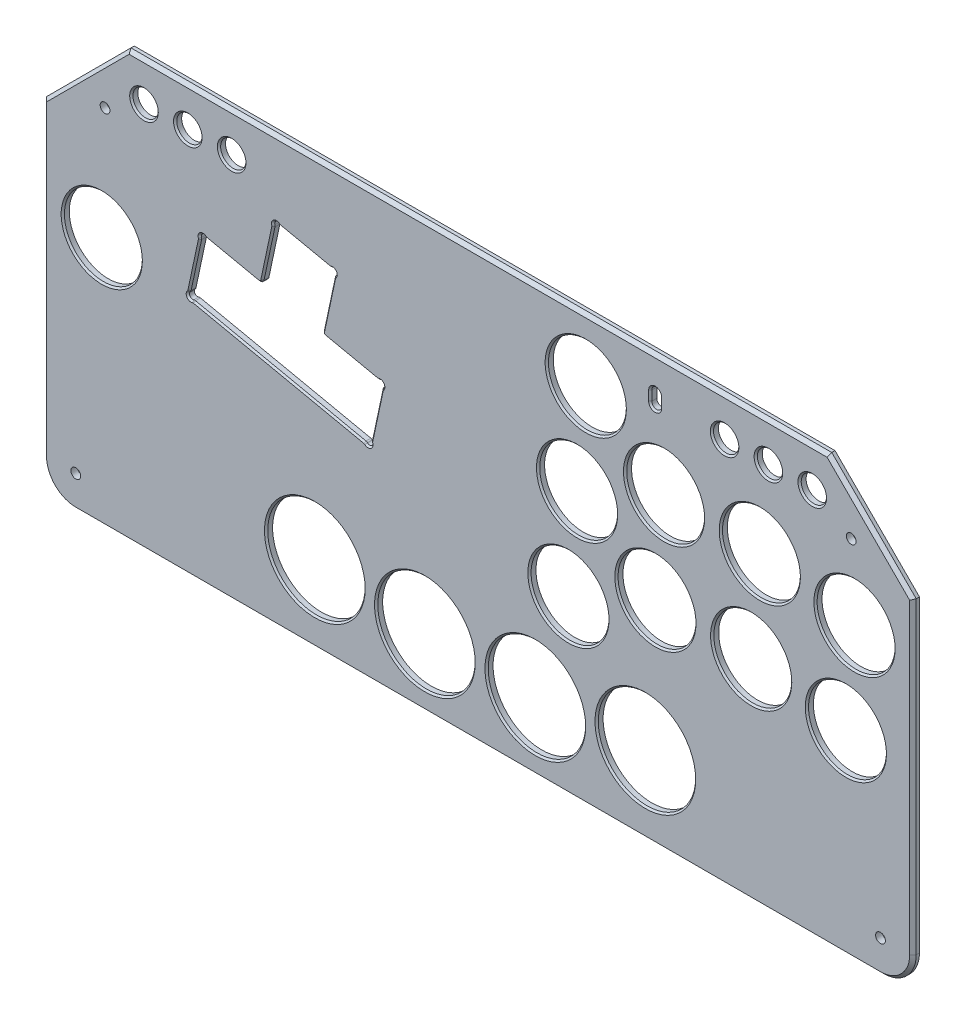
SolidWorks part; units mm, degrees
ref_plane "Front Plane" through (0, 0, 0) normal (0, 0, 1) x (1, 0, 0)
ref_plane "Top Plane" through (0, 0, 0) normal (0, 1, 0) x (1, 0, 0)
ref_plane "Right Plane" through (0, 0, 0) normal (1, 0, 0) x (0, 0, -1)
sketch "Sketch1" plane through (0, 0, 0) normal (0, 0, 1) x (1, 0, 0)
  line L0 (157.8919, 26.2701) -> (191.7747, 29.0915)
  line L1 (157.8919, 26.2701) -> (191.7747, 26.2701)
  line L2 (157.8919, 26.2701) -> (157.8919, 29.0915)
  line L3 (157.8919, 29.0915) -> (191.7747, 29.0915)
  line L4 (191.7747, 26.2701) -> (191.7747, 29.0915)
  line L5 (123.8919, 26.2701) -> (90.0092, 26.2701)
  line L6 (123.8919, 26.2701) -> (123.8919, 29.0915)
  line L7 (123.8919, 29.0915) -> (90.0092, 29.0915)
  line L8 (90.0092, 26.2701) -> (90.0092, 29.0915)
  line L9 (90.0092, 29.0915) -> (123.8919, 26.2701)
  line L10 (168.0919, 58.3601) -> (194.8735, 70.7292)
  line L11 (168.0919, 58.3601) -> (194.8735, 58.3601)
  line L12 (168.0919, 58.3601) -> (168.0919, 70.7292)
  line L13 (168.0919, 70.7292) -> (194.8735, 70.7292)
  line L14 (194.8735, 58.3601) -> (194.8735, 70.7292)
  line L15 (194.8735, 70.7292) -> (224.3587, 70.7292)
  line L16 (194.8735, 70.7292) -> (194.8735, 69.7923)
  line L17 (194.8735, 69.7923) -> (224.3587, 69.7923)
  line L18 (224.3587, 70.7292) -> (224.3587, 69.7923)
  line L19 (224.3587, 69.7923) -> (253.5106, 69.7923)
  line L20 (224.3587, 69.7923) -> (224.3587, 65.2742)
  line L21 (224.3587, 65.2742) -> (253.5106, 65.2742)
  line L22 (253.5106, 69.7923) -> (253.5106, 65.2742)
  line L23 (224.3587, 69.7923) -> (194.8735, 70.7292)
  line L24 (253.5106, 65.2742) -> (224.3587, 69.7923)
  line L25 (170.7502, 87.7401) -> (168.0919, 58.3601)
  line L26 (168.0919, 58.3601) -> (170.7502, 58.3601)
  line L27 (168.0919, 58.3601) -> (168.0919, 87.7401)
  line L28 (168.0919, 87.7401) -> (170.7502, 87.7401)
  line L29 (170.7502, 58.3601) -> (170.7502, 87.7401)
  line L30 (52.9966, 89.4705) -> (24.4119, 82.1791)
  line L31 (24.4119, 82.1791) -> (52.9966, 82.1791)
  line L32 (24.4119, 82.1791) -> (24.4119, 89.4705)
  line L33 (24.4119, 89.4705) -> (52.9966, 89.4705)
  line L34 (52.9966, 82.1791) -> (52.9966, 89.4705)
  line L35 (82.4966, 89.4705) -> (109.0019, 89.4705)
  line L36 (82.4966, 89.4705) -> (82.4966, 76.5201)
  line L37 (82.4966, 76.5201) -> (109.0019, 76.5201)
  line L38 (109.0019, 89.4705) -> (109.0019, 76.5201)
  line L39 (92.4554, 117.2387) -> (82.4966, 117.2387)
  line L40 (92.4554, 117.2387) -> (92.4554, 89.4705)
  line L41 (92.4554, 89.4705) -> (82.4966, 89.4705)
  line L42 (82.4966, 117.2387) -> (82.4966, 89.4705)
  line L43 (92.4554, 117.2387) -> (82.4966, 89.4705)
  line L44 (109.0019, 76.5201) -> (82.4966, 89.4705)
  circle A0 centre (123.8919, 26.2701) radius 14.25
  circle A1 centre (157.8919, 26.2701) radius 14.25
  circle A2 centre (90.0092, 29.0915) radius 14.25
  circle A3 centre (191.7747, 29.0915) radius 14.25
  circle A4 centre (82.4966, 89.4705) radius 11.25
  circle A5 centre (92.4554, 117.2387) radius 11.25
  circle A6 centre (52.9966, 89.4705) radius 11.25
  circle A7 centre (109.0019, 76.5201) radius 11.25
  circle A8 centre (24.4119, 82.1791) radius 11.25
  circle A9 centre (170.7502, 87.7401) radius 11.25
  circle A10 centre (168.0919, 58.3601) radius 11.25
  circle A11 centre (197.5318, 100.1092) radius 11.25
  circle A12 centre (194.8735, 70.7292) radius 11.25
  circle A13 centre (227.0169, 99.1723) radius 11.25
  circle A14 centre (224.3587, 69.7923) radius 11.25
  circle A15 centre (256.1689, 94.6541) radius 11.25
  circle A16 centre (253.5106, 65.2742) radius 11.25
  circle A17 centre (24.4119, 82.1791) radius 12
  circle A18 centre (52.9966, 89.4705) radius 12
  circle A19 centre (92.4554, 117.2387) radius 12
  circle A20 centre (82.4966, 89.4705) radius 12
  circle A21 centre (109.0019, 76.5201) radius 12
  circle A22 centre (168.0919, 58.3601) radius 12
  circle A23 centre (194.8735, 70.7292) radius 12
  circle A24 centre (224.3587, 69.7923) radius 12
  circle A25 centre (253.5106, 65.2742) radius 12
  circle A26 centre (256.1689, 94.6541) radius 12
  circle A27 centre (227.0169, 99.1723) radius 12
  circle A28 centre (197.5318, 100.1092) radius 12
  circle A29 centre (170.7502, 87.7401) radius 12
  circle A30 centre (191.7747, 29.0915) radius 15
  circle A31 centre (157.8919, 26.2701) radius 15
  circle A32 centre (123.8919, 26.2701) radius 15
  circle A33 centre (90.0092, 29.0915) radius 15
  circle A34 centre (173.429, 117.1182) radius 11.25
  circle A35 centre (173.429, 117.1182) radius 12
  dimension "D1" = 28.5
  dimension "D2" = 22.5
  dimension "D3" = 0.75
  dimension "D4" = 0.75
  dimension "D34" = 34
  dimension "D5" = 29.5
  dimension "D6" = 29.5
  dimension "D7" = 29.5
  dimension "D8" = 29.5
  dimension "D9" = 29.5
  dimension "D10" = 29.5
  dimension "D11" = 29.5
  dimension "D12" = 29.5
  dimension "D13" = 29.5
  dimension "D14" = 29.5
  dimension "D15" = 29.5
  dimension "D16" = 29.5
  dimension "D17" = 29.5
  dimension "D18" = 29.5
  dimension "D19" = 34
  dimension "D20" = 34
  dimension "D21" = 32.09
  dimension "D22" = 10.2
  dimension "D23" = 4.76
  dimension "D24" = 4.76
  dimension "D25" = 24.79
  dimension "D26" = 1.82
  dimension "D27" = 8.81
  dimension "D28" = 84.83
  dimension "D29" = 75.69
  dimension "D30" = 70.27
  dimension "D31" = 26.04
  dimension "D32" = 14.89
  dimension "D33" = 50.25
  dimension "D35" = 29.5
  dimension "D36" = 29.5
sketch "Sketch4" plane through (-30.2083, 20.075, 0) normal (0, 0, 1) x (0.9781, -0.2079, 0)
  line L0 (86.1706, 94.1917) -> (105.2206, 75.1417)
  line L1 (67.1206, 94.1917) -> (86.1706, 94.1917)
  line L2 (67.1206, 94.1917) -> (67.1206, 75.1417)
  line L3 (67.1206, 75.1417) -> (86.1706, 75.1417)
  line L4 (86.1706, 94.1917) -> (86.1706, 75.1417)
  line L5 (86.1706, 94.1917) -> (105.2206, 94.1917)
  line L6 (86.1706, 94.1917) -> (86.1706, 75.1417)
  line L7 (86.1706, 75.1417) -> (105.2206, 75.1417)
  line L8 (105.2206, 94.1917) -> (105.2206, 75.1417)
  line L9 (105.2206, 94.1917) -> (124.2706, 94.1917)
  line L10 (105.2206, 94.1917) -> (105.2206, 75.1417)
  line L11 (105.2206, 75.1417) -> (124.2706, 75.1417)
  line L12 (124.2706, 94.1917) -> (124.2706, 75.1417)
  line L13 (86.1706, 94.1917) -> (105.2206, 94.1917)
  line L14 (86.1706, 94.1917) -> (86.1706, 113.2417)
  line L15 (86.1706, 113.2417) -> (105.2206, 113.2417)
  line L16 (105.2206, 94.1917) -> (105.2206, 113.2417)
  line L17 (66.9585, 85.1784) -> (124.4326, 84.1551)
  point P14 (95.6956, 84.6667)
  point P15 (95.6956, 84.6667)
  dimension "D1" = 19.05
sketch "Sketch9" plane through (0, 0, 0) normal (0, 0, 1) x (1, 0, 0)
  line L1 (17.3619, 89.2291) -> (31.4619, 89.2291)
  line L2 (17.3619, 89.2291) -> (17.3619, 75.1291)
  line L3 (17.3619, 75.1291) -> (31.4619, 75.1291)
  line L4 (31.4619, 89.2291) -> (31.4619, 75.1291)
  line L5 (45.9466, 96.5205) -> (60.0466, 96.5205)
  line L6 (45.9466, 96.5205) -> (45.9466, 82.4205)
  line L7 (45.9466, 82.4205) -> (60.0466, 82.4205)
  line L8 (60.0466, 96.5205) -> (60.0466, 82.4205)
  line L9 (75.4466, 96.5205) -> (89.5466, 96.5205)
  line L10 (75.4466, 96.5205) -> (75.4466, 82.4205)
  line L11 (75.4466, 82.4205) -> (89.5466, 82.4205)
  line L12 (89.5466, 96.5205) -> (89.5466, 82.4205)
  line L13 (101.9519, 83.5701) -> (116.0519, 83.5701)
  line L14 (101.9519, 83.5701) -> (101.9519, 69.4701)
  line L15 (101.9519, 69.4701) -> (116.0519, 69.4701)
  line L16 (116.0519, 83.5701) -> (116.0519, 69.4701)
  line L17 (85.4054, 124.2887) -> (99.5054, 124.2887)
  line L18 (85.4054, 124.2887) -> (85.4054, 110.1887)
  line L19 (85.4054, 110.1887) -> (99.5054, 110.1887)
  line L20 (99.5054, 124.2887) -> (99.5054, 110.1887)
  line L21 (82.9592, 36.1415) -> (97.0592, 36.1415)
  line L22 (82.9592, 36.1415) -> (82.9592, 22.0415)
  line L23 (82.9592, 22.0415) -> (97.0592, 22.0415)
  line L24 (97.0592, 36.1415) -> (97.0592, 22.0415)
  line L25 (116.8419, 33.3201) -> (130.9419, 33.3201)
  line L26 (116.8419, 33.3201) -> (116.8419, 19.2201)
  line L27 (116.8419, 19.2201) -> (130.9419, 19.2201)
  line L28 (130.9419, 33.3201) -> (130.9419, 19.2201)
  line L29 (150.8419, 33.3201) -> (164.9419, 33.3201)
  line L30 (150.8419, 33.3201) -> (150.8419, 19.2201)
  line L31 (150.8419, 19.2201) -> (164.9419, 19.2201)
  line L32 (164.9419, 33.3201) -> (164.9419, 19.2201)
  line L33 (184.7247, 36.1415) -> (198.8247, 36.1415)
  line L34 (184.7247, 36.1415) -> (184.7247, 22.0415)
  line L35 (184.7247, 22.0415) -> (198.8247, 22.0415)
  line L36 (198.8247, 36.1415) -> (198.8247, 22.0415)
  line L37 (260.5606, 58.2242) -> (246.4606, 58.2242)
  line L38 (260.5606, 58.2242) -> (260.5606, 72.3242)
  line L39 (260.5606, 72.3242) -> (246.4606, 72.3242)
  line L40 (246.4606, 58.2242) -> (246.4606, 72.3242)
  line L41 (217.3087, 76.8423) -> (231.4087, 76.8423)
  line L42 (217.3087, 76.8423) -> (217.3087, 62.7423)
  line L43 (217.3087, 62.7423) -> (231.4087, 62.7423)
  line L44 (231.4087, 76.8423) -> (231.4087, 62.7423)
  line L45 (187.8235, 77.7792) -> (201.9235, 77.7792)
  line L46 (187.8235, 77.7792) -> (187.8235, 63.6792)
  line L47 (187.8235, 63.6792) -> (201.9235, 63.6792)
  line L48 (201.9235, 77.7792) -> (201.9235, 63.6792)
  line L49 (161.0419, 65.4101) -> (175.1419, 65.4101)
  line L50 (161.0419, 65.4101) -> (161.0419, 51.3101)
  line L51 (161.0419, 51.3101) -> (175.1419, 51.3101)
  line L52 (175.1419, 65.4101) -> (175.1419, 51.3101)
  line L53 (163.7002, 94.7901) -> (177.8002, 94.7901)
  line L54 (163.7002, 94.7901) -> (163.7002, 80.6901)
  line L55 (163.7002, 80.6901) -> (177.8002, 80.6901)
  line L56 (177.8002, 94.7901) -> (177.8002, 80.6901)
  line L57 (190.4818, 107.1592) -> (204.5818, 107.1592)
  line L58 (190.4818, 107.1592) -> (190.4818, 93.0592)
  line L59 (190.4818, 93.0592) -> (204.5818, 93.0592)
  line L60 (204.5818, 107.1592) -> (204.5818, 93.0592)
  line L61 (219.9669, 106.2223) -> (234.0669, 106.2223)
  line L62 (219.9669, 106.2223) -> (219.9669, 92.1223)
  line L63 (219.9669, 92.1223) -> (234.0669, 92.1223)
  line L64 (234.0669, 106.2223) -> (234.0669, 92.1223)
  line L65 (249.1189, 101.7041) -> (263.2189, 101.7041)
  line L66 (249.1189, 101.7041) -> (249.1189, 87.6041)
  line L67 (249.1189, 87.6041) -> (263.2189, 87.6041)
  line L68 (263.2189, 101.7041) -> (263.2189, 87.6041)
  line L69 (166.379, 124.1682) -> (180.479, 124.1682)
  line L70 (166.379, 124.1682) -> (166.379, 110.0682)
  line L71 (166.379, 110.0682) -> (180.479, 110.0682)
  line L72 (180.479, 124.1682) -> (180.479, 110.0682)
  point P72 (24.4119, 89.2291)
  point P74 (52.9966, 96.5205)
  point P76 (82.4966, 96.5205)
  point P78 (92.4554, 124.2887)
  point P80 (109.0019, 83.5701)
  point P82 (90.0092, 36.1415)
  point P84 (123.8919, 33.3201)
  point P86 (157.8919, 33.3201)
  point P88 (191.7747, 36.1415)
  point P90 (168.0919, 65.4101)
  point P92 (170.7502, 94.7901)
  point P94 (173.429, 124.1682)
  point P96 (197.5318, 107.1592)
  point P98 (227.0169, 106.2223)
  point P100 (256.1689, 101.7041)
  point P102 (194.8735, 77.7792)
  point P104 (224.3587, 76.8423)
  point P106 (253.5106, 72.3242)
  point P108 (17.3619, 82.1791)
  point P109 (45.9466, 89.4705)
  point P110 (75.4466, 89.4705)
  point P111 (101.9519, 76.5201)
  point P112 (85.4054, 117.2387)
  point P113 (82.9592, 29.0915)
  point P114 (116.8419, 26.2701)
  point P115 (150.8419, 26.2701)
  point P116 (184.7247, 29.0915)
  point P118 (161.0419, 58.3601)
  point P119 (187.8235, 70.7292)
  point P120 (217.3087, 69.7923)
  point P121 (246.4606, 65.2742)
  point P122 (163.7002, 87.7401)
  point P123 (190.4818, 100.1092)
  point P124 (219.9669, 99.1723)
  point P125 (249.1189, 94.6541)
  point P126 (166.379, 117.1182)
  dimension "D1" = 14.1
sketch "Sketch10" plane through (-22.0981, 19.3454, 0) normal (0, 0, 1) x (0.9781, -0.2079, 0)
  line L1 (61.5108, 90.7441) -> (75.6108, 90.7441)
  line L2 (61.5108, 90.7441) -> (61.5108, 76.6441)
  line L3 (61.5108, 76.6441) -> (75.6108, 76.6441)
  line L4 (75.6108, 90.7441) -> (75.6108, 76.6441)
  line L5 (80.5608, 90.7441) -> (94.6608, 90.7441)
  line L6 (80.5608, 90.7441) -> (80.5608, 76.6441)
  line L7 (80.5608, 76.6441) -> (94.6608, 76.6441)
  line L8 (94.6608, 90.7441) -> (94.6608, 76.6441)
  line L9 (99.6108, 90.7441) -> (113.7108, 90.7441)
  line L10 (99.6108, 90.7441) -> (99.6108, 76.6441)
  line L11 (99.6108, 76.6441) -> (113.7108, 76.6441)
  line L12 (113.7108, 90.7441) -> (113.7108, 76.6441)
  line L13 (80.5608, 109.7941) -> (94.6608, 109.7941)
  line L14 (80.5608, 109.7941) -> (80.5608, 95.6941)
  line L15 (80.5608, 95.6941) -> (94.6608, 95.6941)
  line L16 (94.6608, 109.7941) -> (94.6608, 95.6941)
  line L17 (50.5121, 89.6359) -> (53.4436, 75.8441) construction
  line L18 (59.0358, 93.2191) -> (78.0858, 93.2191) construction
  line L19 (78.0858, 112.2691) -> (97.1358, 112.2691) construction
  line L20 (97.1358, 93.2191) -> (116.1858, 93.2191) construction
  line L21 (78.0858, 93.2191) -> (78.0858, 112.2691) construction
  line L23 (59.0358, 93.2191) -> (59.0358, 74.1691) construction
  point P16 (75.6108, 83.6941)
  point P17 (94.6608, 83.6941)
  point P18 (113.7108, 83.6941)
  point P19 (87.6108, 90.7441)
  point P20 (87.6108, 109.7941)
  point P23 (68.5608, 90.7441)
  point P26 (68.5608, 93.2191)
  point P29 (87.6108, 112.2691)
  point P30 (106.6608, 90.7441)
  point P33 (106.6608, 93.2191)
  point P34 (80.5608, 102.7441)
  point P37 (78.0858, 102.7441)
  point P42 (59.0358, 83.6941)
  point P43 (61.5108, 83.6941)
sketch "Sketch14" plane through (0, 0, 0) normal (0, 0, 1) x (1, 0, 0)
  line L0 (165.1144, 80.6901) -> (163.7002, 82.1043)
  line L1 (163.7002, 93.3758) -> (165.1144, 94.7901)
  line L2 (177.8002, 93.3758) -> (176.386, 94.7901)
  line L3 (179.0648, 110.0682) -> (180.479, 111.4824)
  line L4 (166.379, 111.4824) -> (167.7932, 110.0682)
  line L5 (166.379, 122.754) -> (167.7932, 124.1682)
  line L6 (179.0648, 124.1682) -> (180.479, 122.754)
  line L7 (203.1676, 93.0592) -> (204.5818, 94.4734)
  line L8 (17.3619, 89.2291) -> (17.3619, 75.1291) construction
  line L9 (17.3619, 89.2291) -> (31.4619, 89.2291) construction
  line L10 (17.3619, 87.8149) -> (18.7761, 89.2291)
  line L11 (17.3619, 75.1291) -> (31.4619, 75.1291) construction
  line L12 (31.4619, 89.2291) -> (31.4619, 75.1291) construction
  line L13 (45.9466, 96.5205) -> (60.0466, 96.5205) construction
  line L14 (60.0466, 96.5205) -> (60.0466, 82.4205) construction
  line L15 (45.9466, 96.5205) -> (45.9466, 82.4205) construction
  line L16 (45.9466, 82.4205) -> (60.0466, 82.4205) construction
  line L17 (85.4054, 124.2887) -> (85.4054, 110.1887) construction
  line L18 (85.4054, 124.2887) -> (99.5054, 124.2887) construction
  line L19 (99.5054, 124.2887) -> (99.5054, 110.1887) construction
  line L20 (85.4054, 110.1887) -> (99.5054, 110.1887) construction
  line L21 (101.9519, 83.5701) -> (101.9519, 69.4701) construction
  line L22 (101.9519, 83.5701) -> (116.0519, 83.5701) construction
  line L23 (116.0519, 83.5701) -> (116.0519, 69.4701) construction
  line L24 (101.9519, 69.4701) -> (116.0519, 69.4701) construction
  line L25 (91.2712, 73.6044) -> (105.0631, 70.6729) construction
  line L26 (107.9947, 84.4647) -> (105.0631, 70.6729) construction
  line L27 (94.2028, 87.3963) -> (107.9947, 84.4647) construction
  line L28 (94.2028, 87.3963) -> (91.2712, 73.6044) construction
  line L29 (72.6375, 77.5651) -> (86.4294, 74.6336) construction
  line L30 (89.361, 88.4255) -> (86.4294, 74.6336) construction
  line L31 (75.5691, 91.357) -> (89.361, 88.4255) construction
  line L32 (75.5691, 91.357) -> (72.6375, 77.5651) construction
  line L33 (56.9354, 95.3177) -> (54.0038, 81.5259) construction
  line L34 (56.9354, 95.3177) -> (70.7273, 92.3862) construction
  line L35 (70.7273, 92.3862) -> (67.7957, 78.5943) construction
  line L36 (54.0038, 81.5259) -> (67.7957, 78.5943) construction
  line L37 (76.5983, 96.1988) -> (90.3901, 93.2673) construction
  line L38 (93.3217, 107.0592) -> (90.3901, 93.2673) construction
  line L39 (79.5298, 109.9907) -> (76.5983, 96.1988) construction
  line L40 (79.5298, 109.9907) -> (93.3217, 107.0592) construction
  line L41 (82.9592, 36.1415) -> (82.9592, 22.0415) construction
  line L42 (82.9592, 36.1415) -> (97.0592, 36.1415) construction
  line L43 (82.9592, 22.0415) -> (97.0592, 22.0415) construction
  line L44 (97.0592, 36.1415) -> (97.0592, 22.0415) construction
  line L45 (116.8419, 33.3201) -> (116.8419, 19.2201) construction
  line L46 (116.8419, 33.3201) -> (130.9419, 33.3201) construction
  line L47 (116.8419, 19.2201) -> (130.9419, 19.2201) construction
  line L48 (130.9419, 33.3201) -> (130.9419, 19.2201) construction
  line L49 (150.8419, 33.3201) -> (150.8419, 19.2201) construction
  line L50 (150.8419, 33.3201) -> (164.9419, 33.3201) construction
  line L51 (164.9419, 33.3201) -> (164.9419, 19.2201) construction
  line L52 (150.8419, 19.2201) -> (164.9419, 19.2201) construction
  line L53 (184.7247, 36.1415) -> (184.7247, 22.0415) construction
  line L54 (184.7247, 22.0415) -> (198.8247, 22.0415) construction
  line L55 (198.8247, 36.1415) -> (198.8247, 22.0415) construction
  line L56 (184.7247, 36.1415) -> (198.8247, 36.1415) construction
  line L57 (161.0419, 65.4101) -> (175.1419, 65.4101) construction
  line L58 (175.1419, 65.4101) -> (175.1419, 51.3101) construction
  line L59 (161.0419, 51.3101) -> (175.1419, 51.3101) construction
  line L60 (161.0419, 65.4101) -> (161.0419, 51.3101) construction
  line L61 (187.8235, 77.7792) -> (187.8235, 63.6792) construction
  line L62 (187.8235, 77.7792) -> (201.9235, 77.7792) construction
  line L63 (187.8235, 63.6792) -> (201.9235, 63.6792) construction
  line L64 (201.9235, 77.7792) -> (201.9235, 63.6792) construction
  line L65 (217.3087, 76.8423) -> (217.3087, 62.7423) construction
  line L66 (217.3087, 76.8423) -> (231.4087, 76.8423) construction
  line L67 (231.4087, 76.8423) -> (231.4087, 62.7423) construction
  line L68 (217.3087, 62.7423) -> (231.4087, 62.7423) construction
  line L69 (260.5606, 58.2242) -> (246.4606, 58.2242) construction
  line L70 (260.5606, 58.2242) -> (260.5606, 72.3242) construction
  line L71 (246.4606, 58.2242) -> (246.4606, 72.3242) construction
  line L72 (260.5606, 72.3242) -> (246.4606, 72.3242) construction
  line L73 (249.1189, 101.7041) -> (263.2189, 101.7041) construction
  line L74 (263.2189, 101.7041) -> (263.2189, 87.6041) construction
  line L75 (249.1189, 87.6041) -> (263.2189, 87.6041) construction
  line L76 (249.1189, 101.7041) -> (249.1189, 87.6041) construction
  line L77 (219.9669, 106.2223) -> (219.9669, 92.1223) construction
  line L78 (219.9669, 106.2223) -> (234.0669, 106.2223) construction
  line L79 (234.0669, 106.2223) -> (234.0669, 92.1223) construction
  line L80 (219.9669, 92.1223) -> (234.0669, 92.1223) construction
  line L81 (190.4818, 107.1592) -> (204.5818, 107.1592) construction
  line L82 (204.5818, 107.1592) -> (204.5818, 93.0592) construction
  line L83 (190.4818, 93.0592) -> (204.5818, 93.0592) construction
  line L84 (190.4818, 107.1592) -> (190.4818, 93.0592) construction
  line L85 (163.7002, 94.7901) -> (177.8002, 94.7901) construction
  line L86 (177.8002, 94.7901) -> (177.8002, 80.6901) construction
  line L87 (163.7002, 80.6901) -> (177.8002, 80.6901) construction
  line L88 (163.7002, 94.7901) -> (163.7002, 80.6901) construction
  line L89 (180.479, 124.1682) -> (180.479, 110.0682) construction
  line L90 (166.379, 110.0682) -> (180.479, 110.0682) construction
  line L91 (166.379, 124.1682) -> (166.379, 110.0682) construction
  line L92 (166.379, 124.1682) -> (180.479, 124.1682) construction
  line L93 (17.3619, 76.5433) -> (18.7761, 75.1291)
  line L94 (30.0477, 75.1291) -> (31.4619, 76.5433)
  line L95 (31.4619, 87.8149) -> (30.0477, 89.2291)
  line L96 (45.9466, 95.1063) -> (47.3608, 96.5205)
  line L97 (45.9466, 83.8347) -> (47.3608, 82.4205)
  line L98 (54.2979, 82.9092) -> (55.3871, 81.2318)
  line L99 (58.6323, 82.4205) -> (60.0466, 83.8347)
  line L100 (56.6413, 93.9344) -> (58.3187, 95.0237)
  line L101 (58.6323, 96.5205) -> (60.0466, 95.1063)
  line L102 (69.3439, 92.6802) -> (70.4332, 91.0029)
  line L103 (68.0897, 79.9776) -> (66.4124, 78.8883)
  line L104 (75.2751, 89.9737) -> (76.9524, 91.063)
  line L105 (72.9316, 78.9484) -> (74.0208, 77.2711)
  line L106 (85.0461, 74.9276) -> (86.7234, 76.0169)
  line L107 (89.0669, 87.0421) -> (87.9777, 88.7195)
  line L108 (89.0068, 93.5613) -> (90.6842, 94.6506)
  line L109 (76.8923, 97.5822) -> (77.9816, 95.9048)
  line L110 (91.9384, 107.3532) -> (93.0277, 105.6759)
  line L111 (79.2358, 108.6074) -> (80.9131, 109.6967)
  line L112 (85.4054, 111.6029) -> (86.8196, 110.1887)
  line L113 (98.0912, 110.1887) -> (99.5054, 111.6029)
  line L114 (98.0912, 124.2887) -> (99.5054, 122.8745)
  line L115 (85.4054, 122.8745) -> (86.8196, 124.2887)
  line L116 (93.9088, 86.013) -> (95.5861, 87.1023)
  line L117 (91.5653, 74.9877) -> (92.6546, 73.3104)
  line L118 (103.6798, 70.9669) -> (105.3572, 72.0562)
  line L119 (106.6114, 84.7588) -> (107.7006, 83.0814)
  line L120 (101.9519, 82.1559) -> (103.3662, 83.5701)
  line L121 (101.9519, 70.8843) -> (103.3662, 69.4701)
  line L122 (114.6377, 69.4701) -> (116.0519, 70.8843)
  line L123 (116.0519, 82.1559) -> (114.6377, 83.5701)
  line L124 (82.9592, 34.7272) -> (84.3734, 36.1415)
  line L125 (82.9592, 23.4557) -> (84.3734, 22.0415)
  line L126 (95.645, 22.0415) -> (97.0592, 23.4557)
  line L127 (97.0592, 34.7272) -> (95.645, 36.1415)
  line L128 (116.8419, 31.9059) -> (118.2562, 33.3201)
  line L129 (116.8419, 20.6343) -> (118.2562, 19.2201)
  line L130 (129.5277, 19.2201) -> (130.9419, 20.6343)
  line L131 (130.9419, 31.9059) -> (129.5277, 33.3201)
  line L132 (150.8419, 31.9059) -> (152.2562, 33.3201)
  line L133 (150.8419, 20.6343) -> (152.2562, 19.2201)
  line L134 (163.5277, 19.2201) -> (164.9419, 20.6343)
  line L135 (164.9419, 31.9059) -> (163.5277, 33.3201)
  line L136 (184.7247, 34.7272) -> (186.1389, 36.1415)
  line L137 (184.7247, 23.4557) -> (186.1389, 22.0415)
  line L138 (197.4105, 22.0415) -> (198.8247, 23.4557)
  line L139 (198.8247, 34.7272) -> (197.4105, 36.1415)
  line L140 (173.7277, 51.3101) -> (175.1419, 52.7243)
  line L141 (161.0419, 52.7243) -> (162.4562, 51.3101)
  line L142 (161.0419, 63.9959) -> (162.4562, 65.4101)
  line L143 (173.7277, 65.4101) -> (175.1419, 63.9959)
  line L144 (187.8235, 65.0934) -> (189.2378, 63.6792)
  line L145 (200.5093, 63.6792) -> (201.9235, 65.0934)
  line L146 (200.5093, 77.7792) -> (201.9235, 76.365)
  line L147 (187.8235, 76.365) -> (189.2378, 77.7792)
  line L148 (176.386, 80.6901) -> (177.8002, 82.1043)
  line L149 (204.5818, 105.745) -> (203.1676, 107.1592)
  line L150 (191.896, 107.1592) -> (190.4818, 105.745)
  line L151 (190.4818, 94.4734) -> (191.896, 93.0592)
  line L152 (219.9669, 104.8081) -> (221.3812, 106.2223)
  line L153 (232.6527, 106.2223) -> (234.0669, 104.8081)
  line L154 (234.0669, 93.5365) -> (232.6527, 92.1223)
  line L155 (219.9669, 93.5365) -> (221.3812, 92.1223)
  line L156 (229.9944, 76.8423) -> (231.4087, 75.4281)
  line L157 (217.3087, 75.4281) -> (218.7229, 76.8423)
  line L158 (217.3087, 64.1565) -> (218.7229, 62.7423)
  line L159 (229.9944, 62.7423) -> (231.4087, 64.1565)
  line L160 (259.1464, 72.3242) -> (260.5606, 70.9099)
  line L161 (246.4606, 70.9099) -> (247.8748, 72.3242)
  line L162 (259.1464, 58.2242) -> (260.5606, 59.6384)
  line L163 (247.8748, 58.2242) -> (246.4606, 59.6384)
  line L164 (261.8047, 87.6041) -> (263.2189, 89.0183)
  line L165 (249.1189, 89.0183) -> (250.5331, 87.6041)
  line L166 (249.1189, 100.2899) -> (250.5331, 101.7041)
  line L167 (261.8047, 101.7041) -> (263.2189, 100.2899)
  line L168 (75.4466, 96.5205) -> (75.4466, 82.4205) construction
  line L169 (75.4466, 96.5205) -> (89.5466, 96.5205) construction
  line L170 (89.5466, 96.5205) -> (89.5466, 82.4205) construction
  line L171 (75.4466, 82.4205) -> (89.5466, 82.4205) construction
  line L172 (76.8608, 96.5205) -> (75.4466, 95.1063)
  line L173 (88.1323, 96.5205) -> (89.5466, 95.1063)
  line L174 (89.5466, 83.8347) -> (88.1323, 82.4205)
  line L175 (75.4466, 83.8347) -> (76.8608, 82.4205)
  arc A0 (17.3619, 87.8149) -> (18.7761, 89.2291) centre (18.069, 88.522) cw
  arc A1 (18.7761, 75.1291) -> (17.3619, 76.5433) centre (18.069, 75.8362) cw
  arc A2 (31.4619, 76.5433) -> (30.0477, 75.1291) centre (30.7548, 75.8362) cw
  arc A3 (30.0477, 89.2291) -> (31.4619, 87.8149) centre (30.7548, 88.522) cw
  arc A4 (58.6323, 96.5205) -> (60.0466, 95.1063) centre (59.3394, 95.8134) cw
  arc A5 (45.9466, 95.1063) -> (47.3608, 96.5205) centre (46.6537, 95.8134) cw
  arc A6 (47.3608, 82.4205) -> (45.9466, 83.8347) centre (46.6537, 83.1276) cw
  arc A7 (60.0466, 83.8347) -> (58.6323, 82.4205) centre (59.3394, 83.1276) cw
  arc A8 (85.4054, 122.8745) -> (86.8196, 124.2887) centre (86.1125, 123.5816) cw
  arc A9 (98.0912, 124.2887) -> (99.5054, 122.8745) centre (98.7983, 123.5816) cw
  arc A10 (99.5054, 111.6029) -> (98.0912, 110.1887) centre (98.7983, 110.8958) cw
  arc A11 (85.4054, 111.6029) -> (86.8196, 110.1887) centre (86.1125, 110.8958) ccw
  arc A12 (101.9519, 82.1559) -> (103.3662, 83.5701) centre (102.6591, 82.863) cw
  arc A13 (114.6377, 83.5701) -> (116.0519, 82.1559) centre (115.3448, 82.863) cw
  arc A14 (116.0519, 70.8843) -> (114.6377, 69.4701) centre (115.3448, 70.1772) cw
  arc A15 (101.9519, 70.8843) -> (103.3662, 69.4701) centre (102.6591, 70.1772) ccw
  arc A16 (103.6798, 70.9669) -> (105.3572, 72.0562) centre (104.5185, 71.5115) ccw
  arc A17 (106.6114, 84.7588) -> (107.7006, 83.0814) centre (107.156, 83.9201) cw
  arc A18 (93.9088, 86.013) -> (95.5861, 87.1023) centre (94.7474, 86.5576) cw
  arc A19 (91.5653, 74.9877) -> (92.6546, 73.3104) centre (92.1099, 74.1491) ccw
  arc A20 (85.0461, 74.9276) -> (86.7234, 76.0169) centre (85.8848, 75.4722) ccw
  arc A21 (87.9777, 88.7195) -> (89.0669, 87.0421) centre (88.5223, 87.8808) cw
  arc A22 (75.2751, 89.9737) -> (76.9524, 91.063) centre (76.1137, 90.5183) cw
  arc A23 (72.9316, 78.9484) -> (74.0208, 77.2711) centre (73.4762, 78.1098) ccw
  arc A24 (56.6413, 93.9344) -> (58.3187, 95.0237) centre (57.48, 94.4791) cw
  arc A25 (69.3439, 92.6802) -> (70.4332, 91.0029) centre (69.8886, 91.8415) cw
  arc A26 (68.0897, 79.9776) -> (66.4124, 78.8883) centre (67.2511, 79.433) cw
  arc A27 (54.2979, 82.9092) -> (55.3871, 81.2318) centre (54.8425, 82.0705) ccw
  arc A28 (89.0068, 93.5613) -> (90.6842, 94.6506) centre (89.8455, 94.106) ccw
  arc A29 (76.8923, 97.5822) -> (77.9816, 95.9048) centre (77.4369, 96.7435) ccw
  arc A30 (79.2358, 108.6074) -> (80.9131, 109.6967) centre (80.0744, 109.1521) cw
  arc A31 (91.9384, 107.3532) -> (93.0277, 105.6759) centre (92.483, 106.5145) cw
  arc A32 (82.9592, 34.7272) -> (84.3734, 36.1415) centre (83.6663, 35.4344) cw
  arc A33 (82.9592, 23.4557) -> (84.3734, 22.0415) centre (83.6663, 22.7486) ccw
  arc A34 (95.645, 22.0415) -> (97.0592, 23.4557) centre (96.3521, 22.7486) ccw
  arc A35 (95.645, 36.1415) -> (97.0592, 34.7272) centre (96.3521, 35.4344) cw
  arc A36 (116.8419, 31.9059) -> (118.2562, 33.3201) centre (117.5491, 32.613) cw
  arc A37 (116.8419, 20.6343) -> (118.2562, 19.2201) centre (117.5491, 19.9272) ccw
  arc A38 (129.5277, 19.2201) -> (130.9419, 20.6343) centre (130.2348, 19.9272) ccw
  arc A39 (129.5277, 33.3201) -> (130.9419, 31.9059) centre (130.2348, 32.613) cw
  arc A40 (150.8419, 31.9059) -> (152.2562, 33.3201) centre (151.5491, 32.613) cw
  arc A41 (163.5277, 33.3201) -> (164.9419, 31.9059) centre (164.2348, 32.613) cw
  arc A42 (164.9419, 20.6343) -> (163.5277, 19.2201) centre (164.2348, 19.9272) cw
  arc A43 (150.8419, 20.6343) -> (152.2562, 19.2201) centre (151.5491, 19.9272) ccw
  arc A44 (184.7247, 23.4557) -> (186.1389, 22.0415) centre (185.4318, 22.7486) ccw
  arc A45 (197.4105, 22.0415) -> (198.8247, 23.4557) centre (198.1176, 22.7486) ccw
  arc A46 (197.4105, 36.1415) -> (198.8247, 34.7272) centre (198.1176, 35.4344) cw
  arc A47 (184.7247, 34.7272) -> (186.1389, 36.1415) centre (185.4318, 35.4344) cw
  arc A48 (173.7277, 65.4101) -> (175.1419, 63.9959) centre (174.4348, 64.703) cw
  arc A49 (175.1419, 52.7243) -> (173.7277, 51.3101) centre (174.4348, 52.0172) cw
  arc A50 (161.0419, 52.7243) -> (162.4562, 51.3101) centre (161.7491, 52.0172) ccw
  arc A51 (161.0419, 63.9959) -> (162.4562, 65.4101) centre (161.7491, 64.703) cw
  arc A52 (187.8235, 76.365) -> (189.2378, 77.7792) centre (188.5306, 77.0721) cw
  arc A53 (187.8235, 65.0934) -> (189.2378, 63.6792) centre (188.5306, 64.3863) ccw
  arc A54 (200.5093, 63.6792) -> (201.9235, 65.0934) centre (201.2164, 64.3863) ccw
  arc A55 (200.5093, 77.7792) -> (201.9235, 76.365) centre (201.2164, 77.0721) cw
  arc A56 (217.3087, 75.4281) -> (218.7229, 76.8423) centre (218.0158, 76.1352) cw
  arc A57 (229.9944, 76.8423) -> (231.4087, 75.4281) centre (230.7016, 76.1352) cw
  arc A58 (231.4087, 64.1565) -> (229.9944, 62.7423) centre (230.7016, 63.4494) cw
  arc A59 (217.3087, 64.1565) -> (218.7229, 62.7423) centre (218.0158, 63.4494) ccw
  arc A60 (259.1464, 58.2242) -> (260.5606, 59.6384) centre (259.8535, 58.9313) ccw
  arc A61 (246.4606, 59.6384) -> (247.8748, 58.2242) centre (247.1677, 58.9313) ccw
  arc A62 (246.4606, 70.9099) -> (247.8748, 72.3242) centre (247.1677, 71.617) cw
  arc A63 (259.1464, 72.3242) -> (260.5606, 70.9099) centre (259.8535, 71.617) cw
  arc A64 (261.8047, 101.7041) -> (263.2189, 100.2899) centre (262.5118, 100.997) cw
  arc A65 (263.2189, 89.0183) -> (261.8047, 87.6041) centre (262.5118, 88.3112) cw
  arc A66 (250.5331, 87.6041) -> (249.1189, 89.0183) centre (249.826, 88.3112) cw
  arc A67 (249.1189, 100.2899) -> (250.5331, 101.7041) centre (249.826, 100.997) cw
  arc A68 (219.9669, 104.8081) -> (221.3812, 106.2223) centre (220.674, 105.5152) cw
  arc A69 (232.6527, 106.2223) -> (234.0669, 104.8081) centre (233.3598, 105.5152) cw
  arc A70 (234.0669, 93.5365) -> (232.6527, 92.1223) centre (233.3598, 92.8294) cw
  arc A71 (221.3812, 92.1223) -> (219.9669, 93.5365) centre (220.674, 92.8294) cw
  arc A72 (203.1676, 107.1592) -> (204.5818, 105.745) centre (203.8747, 106.4521) cw
  arc A73 (204.5818, 94.4734) -> (203.1676, 93.0592) centre (203.8747, 93.7663) cw
  arc A74 (191.896, 93.0592) -> (190.4818, 94.4734) centre (191.1889, 93.7663) cw
  arc A75 (190.4818, 105.745) -> (191.896, 107.1592) centre (191.1889, 106.4521) cw
  arc A76 (176.386, 94.7901) -> (177.8002, 93.3758) centre (177.0931, 94.0829) cw
  arc A77 (177.8002, 82.1043) -> (176.386, 80.6901) centre (177.0931, 81.3972) cw
  arc A78 (165.1144, 80.6901) -> (163.7002, 82.1043) centre (164.4073, 81.3972) cw
  arc A79 (163.7002, 93.3758) -> (165.1144, 94.7901) centre (164.4073, 94.0829) cw
  arc A80 (180.479, 111.4824) -> (179.0648, 110.0682) centre (179.7719, 110.7753) cw
  arc A81 (167.7932, 110.0682) -> (166.379, 111.4824) centre (167.0861, 110.7753) cw
  arc A82 (179.0648, 124.1682) -> (180.479, 122.754) centre (179.7719, 123.4611) cw
  arc A83 (166.379, 122.754) -> (167.7932, 124.1682) centre (167.0861, 123.4611) cw
  arc A84 (75.4466, 95.1063) -> (76.8608, 96.5205) centre (76.1537, 95.8134) cw
  arc A85 (88.1323, 96.5205) -> (89.5466, 95.1063) centre (88.8394, 95.8134) cw
  arc A86 (89.5466, 83.8347) -> (88.1323, 82.4205) centre (88.8394, 83.1276) cw
  arc A87 (76.8608, 82.4205) -> (75.4466, 83.8347) centre (76.1537, 83.1276) cw
  dimension "D1" = 45
  dimension "D2" = 1
  dimension "D71" = 45
  dimension "D3" = 45
  dimension "D4" = 45
  dimension "D5" = 45
  dimension "D6" = 45
  dimension "D7" = 45
  dimension "D8" = 45
  dimension "D9" = 45
  dimension "D10" = 45
  dimension "D11" = 45
  dimension "D12" = 45
  dimension "D13" = 45
  dimension "D14" = 45
  dimension "D15" = 45
  dimension "D16" = 45
  dimension "D17" = 45
  dimension "D18" = 45
  dimension "D19" = 45
  dimension "D20" = 45
  dimension "D21" = 45
  dimension "D22" = 45
  dimension "D23" = 45
  dimension "D24" = 45
  dimension "D25" = 45
  dimension "D26" = 45
  dimension "D27" = 45
  dimension "D28" = 45
  dimension "D29" = 45
  dimension "D30" = 45
  dimension "D31" = 45
  dimension "D32" = 45
  dimension "D33" = 45
  dimension "D34" = 45
  dimension "D35" = 45
  dimension "D36" = 45
  dimension "D37" = 45
  dimension "D38" = 45
  dimension "D39" = 45
  dimension "D40" = 45
  dimension "D41" = 45
  dimension "D42" = 45
  dimension "D43" = 45
  dimension "D44" = 45
  dimension "D45" = 45
  dimension "D46" = 45
  dimension "D47" = 45
  dimension "D48" = 45
  dimension "D49" = 45
  dimension "D50" = 45
  dimension "D51" = 45
  dimension "D52" = 45
  dimension "D53" = 45
  dimension "D54" = 45
  dimension "D55" = 45
  dimension "D56" = 45
  dimension "D57" = 45
  dimension "D58" = 45
  dimension "D59" = 45
  dimension "D60" = 45
  dimension "D61" = 45
  dimension "D62" = 45
  dimension "D63" = 45
  dimension "D64" = 45
  dimension "D65" = 45
  dimension "D66" = 45
  dimension "D67" = 45
  dimension "D68" = 45
  dimension "D69" = 45
  dimension "D70" = 45
  dimension "D72" = 45
  dimension "D73" = 45
  dimension "D74" = 45
  dimension "D75" = 45
  dimension "D76" = 45
  dimension "D77" = 45
  dimension "D78" = 45
  dimension "D79" = 45
  dimension "D80" = 45
  dimension "D81" = 45
  dimension "D82" = 45
  dimension "D83" = 45
  dimension "D84" = 45
  dimension "D85" = 45
  dimension "D86" = 45
  dimension "D87" = 45
  dimension "D88" = 45
  dimension "D89" = 45
sketch "Sketch16" plane through (0, 0, 0) normal (0, 0, 1) x (1, 0, 0)
  line L0 (81.0092, 30.6915) -> (99.0092, 30.6915)
  line L5 (17.3619, 89.2291) -> (17.3619, 75.1291) construction
  line L6 (81.0092, 30.6915) -> (81.0092, 27.4915)
  line L7 (17.3619, 75.1291) -> (31.4619, 75.1291) construction
  line L8 (15.4119, 83.7791) -> (33.4119, 83.7791)
  line L9 (15.4119, 83.7791) -> (15.4119, 80.5791)
  line L10 (15.4119, 80.5791) -> (33.4119, 80.5791)
  line L11 (33.4119, 83.7791) -> (33.4119, 80.5791)
  line L12 (81.0092, 27.4915) -> (99.0092, 27.4915)
  line L13 (99.0092, 30.6915) -> (99.0092, 27.4915)
  line L14 (114.8919, 27.8701) -> (132.8919, 27.8701)
  line L15 (114.8919, 27.8701) -> (114.8919, 24.6701)
  line L16 (114.8919, 24.6701) -> (132.8919, 24.6701)
  line L17 (132.8919, 27.8701) -> (132.8919, 24.6701)
  line L18 (148.8919, 27.8701) -> (166.8919, 27.8701)
  line L19 (148.8919, 27.8701) -> (148.8919, 24.6701)
  line L20 (148.8919, 24.6701) -> (166.8919, 24.6701)
  line L21 (166.8919, 27.8701) -> (166.8919, 24.6701)
  line L22 (182.7747, 30.6915) -> (200.7747, 30.6915)
  line L23 (182.7747, 30.6915) -> (182.7747, 27.4915)
  line L24 (182.7747, 27.4915) -> (200.7747, 27.4915)
  line L25 (200.7747, 30.6915) -> (200.7747, 27.4915)
  line L26 (43.9966, 91.0705) -> (61.9966, 91.0705)
  line L27 (43.9966, 91.0705) -> (43.9966, 87.8705)
  line L28 (43.9966, 87.8705) -> (61.9966, 87.8705)
  line L29 (61.9966, 91.0705) -> (61.9966, 87.8705)
  line L30 (73.4966, 91.0705) -> (91.4966, 91.0705)
  line L31 (73.4966, 91.0705) -> (73.4966, 87.8705)
  line L32 (73.4966, 87.8705) -> (91.4966, 87.8705)
  line L33 (91.4966, 91.0705) -> (91.4966, 87.8705)
  line L34 (100.0019, 78.1201) -> (118.0019, 78.1201)
  line L35 (100.0019, 78.1201) -> (100.0019, 74.9201)
  line L36 (100.0019, 74.9201) -> (118.0019, 74.9201)
  line L37 (118.0019, 78.1201) -> (118.0019, 74.9201)
  line L38 (83.4554, 118.8387) -> (101.4554, 118.8387)
  line L39 (83.4554, 118.8387) -> (83.4554, 115.6387)
  line L40 (83.4554, 115.6387) -> (101.4554, 115.6387)
  line L41 (101.4554, 118.8387) -> (101.4554, 115.6387)
  line L42 (164.429, 118.7182) -> (182.429, 118.7182)
  line L43 (164.429, 118.7182) -> (164.429, 115.5182)
  line L44 (164.429, 115.5182) -> (182.429, 115.5182)
  line L45 (182.429, 118.7182) -> (182.429, 115.5182)
  line L46 (161.7502, 89.3401) -> (179.7502, 89.3401)
  line L47 (161.7502, 89.3401) -> (161.7502, 86.1401)
  line L48 (161.7502, 86.1401) -> (179.7502, 86.1401)
  line L49 (179.7502, 89.3401) -> (179.7502, 86.1401)
  line L50 (188.5318, 101.7092) -> (206.5318, 101.7092)
  line L51 (188.5318, 101.7092) -> (188.5318, 98.5092)
  line L52 (188.5318, 98.5092) -> (206.5318, 98.5092)
  line L53 (206.5318, 101.7092) -> (206.5318, 98.5092)
  line L54 (159.0919, 59.9601) -> (177.0919, 59.9601)
  line L55 (159.0919, 59.9601) -> (159.0919, 56.7601)
  line L56 (159.0919, 56.7601) -> (177.0919, 56.7601)
  line L57 (177.0919, 59.9601) -> (177.0919, 56.7601)
  line L58 (185.8735, 72.3292) -> (203.8735, 72.3292)
  line L59 (185.8735, 72.3292) -> (185.8735, 69.1292)
  line L60 (185.8735, 69.1292) -> (203.8735, 69.1292)
  line L61 (203.8735, 72.3292) -> (203.8735, 69.1292)
  line L62 (218.0169, 100.7723) -> (236.0169, 100.7723)
  line L63 (218.0169, 100.7723) -> (218.0169, 97.5723)
  line L64 (218.0169, 97.5723) -> (236.0169, 97.5723)
  line L65 (236.0169, 100.7723) -> (236.0169, 97.5723)
  line L66 (215.3587, 71.3923) -> (233.3587, 71.3923)
  line L67 (215.3587, 71.3923) -> (215.3587, 68.1923)
  line L68 (215.3587, 68.1923) -> (233.3587, 68.1923)
  line L69 (233.3587, 71.3923) -> (233.3587, 68.1923)
  line L70 (247.1689, 96.2541) -> (265.1689, 96.2541)
  line L71 (247.1689, 96.2541) -> (247.1689, 93.0541)
  line L72 (247.1689, 93.0541) -> (265.1689, 93.0541)
  line L73 (265.1689, 96.2541) -> (265.1689, 93.0541)
  line L74 (244.5106, 66.8742) -> (262.5106, 66.8742)
  line L75 (244.5106, 66.8742) -> (244.5106, 63.6742)
  line L76 (244.5106, 63.6742) -> (262.5106, 63.6742)
  line L77 (262.5106, 66.8742) -> (262.5106, 63.6742)
  circle A0 centre (15.4119, 82.1791) radius 1.6
  circle A1 centre (33.4119, 82.1791) radius 1.6
  circle A2 centre (81.0092, 29.0915) radius 1.6
  circle A3 centre (99.0092, 29.0915) radius 1.6
  circle A4 centre (114.8919, 26.2701) radius 1.6
  circle A5 centre (132.8919, 26.2701) radius 1.6
  circle A6 centre (148.8919, 26.2701) radius 1.6
  circle A7 centre (166.8919, 26.2701) radius 1.6
  circle A8 centre (182.7747, 29.0915) radius 1.6
  circle A9 centre (200.7747, 29.0915) radius 1.6
  circle A10 centre (43.9966, 89.4705) radius 1.6
  circle A11 centre (61.9966, 89.4705) radius 1.6
  circle A12 centre (73.4966, 89.4705) radius 1.6
  circle A13 centre (91.4966, 89.4705) radius 1.6
  circle A14 centre (100.0019, 76.5201) radius 1.6
  circle A15 centre (118.0019, 76.5201) radius 1.6
  circle A16 centre (83.4554, 117.2387) radius 1.6
  circle A17 centre (101.4554, 117.2387) radius 1.6
  circle A18 centre (164.429, 117.1182) radius 1.6
  circle A19 centre (182.429, 117.1182) radius 1.6
  circle A20 centre (161.7502, 87.7401) radius 1.6
  circle A21 centre (179.7502, 87.7401) radius 1.6
  circle A22 centre (188.5318, 100.1092) radius 1.6
  circle A23 centre (206.5318, 100.1092) radius 1.6
  circle A24 centre (159.0919, 58.3601) radius 1.6
  circle A25 centre (177.0919, 58.3601) radius 1.6
  circle A26 centre (185.8735, 70.7292) radius 1.6
  circle A27 centre (203.8735, 70.7292) radius 1.6
  circle A28 centre (218.0169, 99.1723) radius 1.6
  circle A29 centre (236.0169, 99.1723) radius 1.6
  circle A30 centre (215.3587, 69.7923) radius 1.6
  circle A31 centre (233.3587, 69.7923) radius 1.6
  circle A32 centre (247.1689, 94.6541) radius 1.6
  circle A33 centre (265.1689, 94.6541) radius 1.6
  circle A34 centre (244.5106, 65.2742) radius 1.6
  circle A35 centre (262.5106, 65.2742) radius 1.6
  point P2 (24.4119, 75.1291)
  point P6 (17.3619, 82.1791)
  point P14 (24.4119, 80.5791)
  point P53 (90.0092, 30.6915)
  point P57 (123.8919, 27.8701)
  point P60 (157.8919, 27.8701)
  point P63 (191.7747, 30.6915)
  point P73 (52.9966, 91.0705)
  point P83 (82.4966, 91.0705)
  point P93 (109.0019, 78.1201)
  point P103 (92.4554, 118.8387)
  point P113 (173.429, 118.7182)
  point P123 (170.7502, 89.3401)
  point P133 (197.5318, 101.7092)
  point P143 (168.0919, 59.9601)
  point P153 (194.8735, 72.3292)
  point P163 (227.0169, 100.7723)
  point P173 (224.3587, 71.3923)
  point P183 (256.1689, 96.2541)
  point P193 (253.5106, 66.8742)
  dimension "D1" = 3.2
  dimension "D2" = 18
sketch "Sketch8" plane through (0, 0, 0) normal (0, 0, 1) x (1, 0, 0)
  line L0 (52.2844, 74.6389) -> (82.4966, 89.4705)
  line L1 (86.9403, 110.9459) -> (79.0189, 73.6784)
  line L2 (77.6235, 112.9262) -> (96.2572, 108.9655) construction
  line L3 (69.702, 75.6588) -> (88.3357, 71.6981) construction
  line L4 (53.3861, 72.3947) -> (55.5425, 73.4534)
  line L5 (99.6829, 63.2465) -> (101.1557, 61.3487)
  line L6 (103.1308, 62.8814) -> (82.4966, 89.4705)
  line L13 (93.9017, 130.158) -> (94.0202, 130.4883)
  line L14 (99.5495, 128.1325) -> (99.6679, 128.4628)
  line L16 (99.4417, 62.7418) -> (100.7607, 61.0421)
  line L17 (55.5377, 72.894) -> (53.6064, 71.9459)
  line L19 (82.4966, 89.4705) -> (96.8441, 129.4755)
  circle A1 centre (57.4203, 106.4022) radius 2.5
  circle A2 centre (106.0456, 106.2134) radius 2.5
  circle A3 centre (76.7673, 63.0854) radius 2.5
  circle A4 centre (52.9966, 89.4705) radius 13
  circle A6 centre (92.4554, 117.2387) radius 13
  circle A7 centre (109.0019, 76.5201) radius 13
  circle A8 centre (82.4966, 89.4705) radius 25
  arc A10 (50.3337, 102.1949) -> (81.377, 124.0408) centre (40.5107, 149.1329) ccw
  circle A11 centre (103.1308, 62.8814) radius 2.5
  circle A12 centre (52.2844, 74.6389) radius 2.5
  circle A13 centre (96.8441, 129.4755) radius 2.5
  circle A14 centre (52.2844, 74.6389) radius 3
  circle A15 centre (103.1308, 62.8814) radius 3
  circle A16 centre (96.8441, 129.4755) radius 3
  arc A17 (104.9258, 113.5659) -> (115.3756, 87.8504) centre (126.3001, 107.2707) ccw
  arc A18 (45.7038, 78.7088) -> (110.8301, 63.6492) centre (97.7768, 155.5511) ccw
  circle A19 centre (92.4554, 117.2387) radius 15
  circle A20 centre (109.0019, 76.5201) radius 15
  circle A21 centre (52.9966, 89.4705) radius 15
  circle A22 centre (82.4966, 89.4705) radius 27
  arc A23 (44.5818, 77.0531) -> (111.1113, 61.6691) centre (97.7768, 155.5511) ccw
  arc A24 (49.924, 104.1525) -> (79.6727, 125.0873) centre (40.5107, 149.1329) ccw
  arc A25 (106.8443, 113.0008) -> (116.3562, 89.5935) centre (126.3001, 107.2707) ccw
  circle A26 centre (52.9966, 89.4705) radius 12.5
  circle A27 centre (109.0019, 76.5201) radius 12.5
  circle A28 centre (92.4554, 117.2387) radius 12.5
  circle A29 centre (82.4966, 89.4705) radius 24.5
  arc A30 (104.4462, 113.7071) -> (115.1305, 87.4146) centre (126.3001, 107.2707) ccw
  arc A31 (110.7597, 64.1443) -> (45.9842, 79.1227) centre (97.7768, 155.5511) cw
  arc A32 (50.4361, 101.7055) -> (81.8031, 123.7792) centre (40.5107, 149.1329) ccw
  circle A33 centre (52.9966, 89.4705) radius 15.5
  circle A34 centre (109.0019, 76.5201) radius 15.5
  circle A35 centre (92.4554, 117.2387) radius 15.5
  circle A36 centre (82.4966, 89.4705) radius 27.5
  arc A37 (107.3239, 112.8596) -> (116.6013, 90.0293) centre (126.3001, 107.2707) ccw
  arc A38 (111.1816, 61.1741) -> (44.3013, 76.6392) centre (97.7768, 155.5511) cw
  arc A39 (49.8216, 104.6419) -> (79.2466, 125.349) centre (40.5107, 149.1329) ccw
  circle A40 centre (106.0456, 106.2134) radius 3
  circle A41 centre (76.7673, 63.0854) radius 3
  circle A42 centre (57.4203, 106.4022) radius 3
  dimension "D3" = 26
  dimension "D4" = 5
  dimension "D7" = 6
  dimension "D8" = 50
  dimension "D1" = 2
  dimension "D2" = 2
  dimension "D5" = 0.5
  dimension "D6" = 0.5
  dimension "D9" = 0.5
  dimension "D10" = 0.5
sketch "Sketch2" plane through (0, 0, 0) normal (0, 0, 1) x (1, 0, 0)
  line L0 (30.4119, 134.2387) -> (8.4119, 112.2387)
  line L1 (16.4119, 134.2387) -> (264.1689, 134.2387)
  line L2 (8.4119, 126.2387) -> (8.4119, 15.2864)
  line L3 (16.4119, 7.2864) -> (264.1689, 7.2864)
  line L4 (272.1689, 126.2387) -> (272.1689, 15.2864)
  line L5 (16.4119, 136.2387) -> (264.1689, 136.2387)
  line L6 (6.4119, 126.2387) -> (6.4119, 15.2864)
  line L7 (16.4119, 5.2864) -> (264.1689, 5.2864)
  line L8 (274.1689, 126.2387) -> (274.1689, 15.2864)
  line L9 (250.1689, 134.2387) -> (272.1689, 112.2387)
  line L10 (6.4119, 110.2387) -> (32.4119, 136.2387)
  line L11 (248.1689, 136.2387) -> (274.1689, 110.2387)
  line L12 (6.4119, 107.4103) -> (35.2403, 136.2387)
  line L13 (245.3405, 136.2387) -> (274.1689, 107.4103)
  circle A0 centre (24.4119, 82.1791) radius 12 construction
  circle A2 centre (256.1689, 94.6541) radius 12 construction
  arc A3 (264.1689, 136.2387) -> (274.1689, 126.2387) centre (264.1689, 126.2387) cw
  circle A4 centre (123.8919, 26.2701) radius 15 construction
  arc A5 (264.1689, 5.2864) -> (274.1689, 15.2864) centre (264.1689, 15.2864) ccw
  arc A6 (6.4119, 15.2864) -> (16.4119, 5.2864) centre (16.4119, 15.2864) ccw
  arc A7 (16.4119, 136.2387) -> (6.4119, 126.2387) centre (16.4119, 126.2387) ccw
  arc A8 (264.1689, 134.2387) -> (272.1689, 126.2387) centre (264.1689, 126.2387) cw
  arc A9 (264.1689, 7.2864) -> (272.1689, 15.2864) centre (264.1689, 15.2864) ccw
  arc A10 (8.4119, 15.2864) -> (16.4119, 7.2864) centre (16.4119, 15.2864) ccw
  arc A11 (16.4119, 134.2387) -> (8.4119, 126.2387) centre (16.4119, 126.2387) ccw
  circle A12 centre (92.4554, 117.2387) radius 13 construction
  point P4 (12.4119, 82.1791)
  point P5 (92.4554, 130.2387)
  point P8 (268.1689, 94.6541)
  point P14 (124.5912, 11.2864)
  point P36 (30.4119, 134.2387)
  point P39 (250.1689, 134.2387)
  dimension "D9" = 10
  dimension "D10" = 8
  dimension "D1" = 4
  dimension "D2" = 4
  dimension "D3" = 4
  dimension "D4" = 4
  dimension "D5" = 2
  dimension "D6" = 2
  dimension "D7" = 2
  dimension "D8" = 2
  dimension "D11" = 14
  dimension "D12" = 45
  dimension "D13" = 14
  dimension "D14" = 45
  dimension "D15" = 2
  dimension "D16" = 2
sketch "Sketch6" plane through (0, 0, 0) normal (0, 0, 1) x (1, 0, 0)
  line L0 (44.9119, 130.2387) -> (56.9119, 130.2387)
  line L1 (31.4119, 130.2387) -> (43.4119, 130.2387)
  line L2 (31.4119, 130.2387) -> (31.4119, 118.2387)
  line L3 (31.4119, 118.2387) -> (43.4119, 118.2387)
  line L4 (43.4119, 130.2387) -> (43.4119, 118.2387)
  line L5 (34.1619, 133.2387) -> (40.6619, 133.2387)
  line L6 (34.1619, 133.2387) -> (34.1619, 115.2387)
  line L7 (34.1619, 115.2387) -> (40.6619, 115.2387)
  line L8 (40.6619, 133.2387) -> (40.6619, 115.2387)
  line L9 (44.9119, 130.2387) -> (44.9119, 118.2387)
  line L10 (44.9119, 118.2387) -> (56.9119, 118.2387)
  line L11 (56.9119, 130.2387) -> (56.9119, 118.2387)
  line L12 (47.6619, 133.2387) -> (54.1619, 133.2387)
  line L13 (47.6619, 133.2387) -> (47.6619, 115.2387)
  line L14 (47.6619, 115.2387) -> (54.1619, 115.2387)
  line L15 (54.1619, 133.2387) -> (54.1619, 115.2387)
  line L16 (58.4119, 130.2387) -> (70.4119, 130.2387)
  line L17 (58.4119, 130.2387) -> (58.4119, 118.2387)
  line L18 (58.4119, 118.2387) -> (70.4119, 118.2387)
  line L19 (70.4119, 130.2387) -> (70.4119, 118.2387)
  line L20 (61.1619, 133.2387) -> (67.6619, 133.2387)
  line L21 (61.1619, 133.2387) -> (61.1619, 115.2387)
  line L22 (61.1619, 115.2387) -> (67.6619, 115.2387)
  line L23 (67.6619, 133.2387) -> (67.6619, 115.2387)
  line L24 (237.1689, 130.2387) -> (249.1689, 130.2387)
  line L25 (237.1689, 130.2387) -> (237.1689, 118.2387)
  line L26 (237.1689, 118.2387) -> (249.1689, 118.2387)
  line L27 (249.1689, 130.2387) -> (249.1689, 118.2387)
  line L28 (239.9189, 133.2387) -> (246.4189, 133.2387)
  line L29 (239.9189, 133.2387) -> (239.9189, 115.2387)
  line L30 (239.9189, 115.2387) -> (246.4189, 115.2387)
  line L31 (246.4189, 133.2387) -> (246.4189, 115.2387)
  line L32 (223.6689, 130.2387) -> (235.6689, 130.2387)
  line L33 (223.6689, 130.2387) -> (223.6689, 118.2387)
  line L34 (223.6689, 118.2387) -> (235.6689, 118.2387)
  line L35 (235.6689, 130.2387) -> (235.6689, 118.2387)
  line L36 (226.4189, 133.2387) -> (232.9189, 133.2387)
  line L37 (226.4189, 133.2387) -> (226.4189, 115.2387)
  line L38 (226.4189, 115.2387) -> (232.9189, 115.2387)
  line L39 (232.9189, 133.2387) -> (232.9189, 115.2387)
  line L40 (210.1689, 130.2387) -> (222.1689, 130.2387)
  line L41 (210.1689, 130.2387) -> (210.1689, 118.2387)
  line L42 (210.1689, 118.2387) -> (222.1689, 118.2387)
  line L43 (222.1689, 130.2387) -> (222.1689, 118.2387)
  line L44 (212.9189, 133.2387) -> (219.4189, 133.2387)
  line L45 (212.9189, 133.2387) -> (212.9189, 115.2387)
  line L46 (212.9189, 115.2387) -> (219.4189, 115.2387)
  line L47 (219.4189, 133.2387) -> (219.4189, 115.2387)
  line L48 (16.4119, 134.2387) -> (264.1689, 134.2387) construction
  line L49 (8.4119, 126.2387) -> (8.4119, 15.2864) construction
  line L50 (272.1689, 126.2387) -> (272.1689, 15.2864) construction
  circle A0 centre (37.4119, 124.2387) radius 3.4
  circle A1 centre (50.9119, 124.2387) radius 3.4
  circle A2 centre (64.4119, 124.2387) radius 3.4
  circle A3 centre (243.1689, 124.2387) radius 3.4
  circle A4 centre (229.6689, 124.2387) radius 3.4
  circle A5 centre (216.1689, 124.2387) radius 3.4
  point P8 (37.4119, 130.2387)
  point P9 (37.4119, 133.2387)
  point P10 (34.1619, 124.2387)
  point P11 (31.4119, 124.2387)
  point P15 (43.4119, 124.2387)
  point P43 (243.1689, 130.2387)
  point P44 (243.1689, 133.2387)
  point P45 (239.9189, 124.2387)
  point P46 (237.1689, 124.2387)
  point P50 (249.1689, 124.2387)
  dimension "D4" = 6.8
  dimension "D9" = 6.8
  dimension "D1" = 18
  dimension "D2" = 12
  dimension "D3" = 6.5
  dimension "D5" = 3
  dimension "D6" = 18
  dimension "D7" = 12
  dimension "D8" = 6.5
  dimension "D11" = 1
  dimension "D12" = 23
  dimension "D13" = 23
  dimension "D10" = 3
sketch "Sketch13" plane through (0, 0, 0) normal (0, 0, 1) x (1, 0, 0)
  line L1 (115.4554, 133.7387) -> (125.4554, 133.7387)
  line L2 (110.4554, 128.7387) -> (110.4554, 118.7387)
  line L3 (115.4554, 113.7387) -> (125.4554, 113.7387)
  line L4 (130.4554, 128.7387) -> (130.4554, 118.7387)
  line L5 (115.9854, 134.7387) -> (124.9254, 134.7387)
  line L6 (115.9854, 134.7387) -> (115.9854, 127.3887)
  line L7 (115.9854, 127.3887) -> (124.9254, 127.3887)
  line L8 (124.9254, 134.7387) -> (124.9254, 127.3887)
  line L9 (115.5354, 132.9887) -> (116.4354, 132.9887)
  line L10 (115.5354, 132.9887) -> (115.5354, 131.2887)
  line L11 (115.5354, 131.2887) -> (116.4354, 131.2887)
  line L12 (116.4354, 132.9887) -> (116.4354, 131.2887)
  line L13 (114.4554, 120.2387) -> (126.4554, 120.2387)
  line L14 (114.4554, 120.2387) -> (114.4554, 113.7387)
  line L15 (114.4554, 113.7387) -> (126.4554, 113.7387)
  line L16 (126.4554, 120.2387) -> (126.4554, 113.7387)
  line L19 (115.4554, 134.2387) -> (125.4554, 134.2387)
  line L20 (109.9554, 128.7387) -> (109.9554, 118.7387)
  line L21 (115.4554, 113.2387) -> (125.4554, 113.2387)
  line L22 (130.9554, 128.7387) -> (130.9554, 118.7387)
  line L23 (16.4119, 134.2387) -> (264.1689, 134.2387) construction
  arc A0 (125.4554, 134.2387) -> (130.9554, 128.7387) centre (125.4554, 128.7387) cw
  arc A1 (115.4554, 133.7387) -> (110.4554, 128.7387) centre (115.4554, 128.7387) ccw
  arc A2 (125.4554, 133.7387) -> (130.4554, 128.7387) centre (125.4554, 128.7387) cw
  arc A3 (125.4554, 113.7387) -> (130.4554, 118.7387) centre (125.4554, 118.7387) ccw
  arc A4 (110.4554, 118.7387) -> (115.4554, 113.7387) centre (115.4554, 118.7387) ccw
  circle A6 centre (112.9554, 123.7387) radius 2.5
  circle A7 centre (127.9554, 123.7387) radius 2.5
  arc A8 (125.4554, 113.2387) -> (130.9554, 118.7387) centre (125.4554, 118.7387) ccw
  arc A9 (109.9554, 118.7387) -> (115.4554, 113.2387) centre (115.4554, 118.7387) ccw
  arc A10 (115.4554, 134.2387) -> (109.9554, 128.7387) centre (115.4554, 128.7387) ccw
  circle A12 centre (92.4554, 117.2387) radius 15.5 construction
  point P9 (115.9854, 132.1387)
  point P13 (116.4354, 132.1387)
  point P14 (115.9854, 132.9887)
  point P15 (120.4554, 113.7387)
  point P16 (120.4554, 127.3887)
  point P17 (120.4554, 113.7387)
  point P34 (110.4554, 123.7387)
  point P41 (120.4554, 134.2387)
  point P42 (120.4554, 133.7387)
  point P43 (130.9554, 123.7387)
  point P44 (130.4554, 123.7387)
  point P53 (107.9554, 117.2387)
  dimension "D7" = 6.5
  dimension "D10" = 5
  dimension "D11" = 5
  dimension "D17" = 5.5
  dimension "D1" = 8.94
  dimension "D2" = 7.35
  dimension "D3" = 2.6
  dimension "D4" = 1.7
  dimension "D5" = 0.9
  dimension "D6" = 1
  dimension "D8" = 12
  dimension "D9" = 7.15
  dimension "D12" = 20
  dimension "D13" = 20
  dimension "D14" = 2
  dimension "D15" = 0.5
  dimension "D16" = 0.5
sketch "Sketch5" plane through (0, 0, 0) normal (0, 0, 1) x (1, 0, 0)
  line L0 (130.9554, 128.7387) -> (130.9554, 118.7387) construction
  line L1 (136.9554, 138.2387) -> (158.5554, 138.2387)
  line L2 (136.9554, 138.2387) -> (136.9554, 106.9387)
  line L3 (136.9554, 106.9387) -> (158.5554, 106.9387)
  line L4 (158.5554, 138.2387) -> (158.5554, 106.9387)
  line L5 (141.7554, 106.9387) -> (153.7554, 106.9387)
  line L6 (141.7554, 106.9387) -> (141.7554, 93.2387)
  line L7 (141.7554, 93.2387) -> (153.7554, 93.2387)
  line L8 (153.7554, 106.9387) -> (153.7554, 93.2387)
  line L9 (16.4119, 136.2387) -> (264.1689, 136.2387) construction
  line L11 (139.9804, 102.2387) -> (155.5304, 102.2387)
  line L12 (139.9804, 102.2387) -> (139.9804, 91.2387)
  line L13 (139.9804, 91.2387) -> (155.5304, 91.2387)
  line L14 (155.5304, 102.2387) -> (155.5304, 91.2387)
  point P8 (147.7554, 106.9387)
  point P9 (147.7554, 106.9387)
  point P18 (147.7554, 93.2387)
  point P19 (147.7554, 102.2387)
  dimension "D1" = 6
  dimension "D2" = 2
  dimension "D3" = 31.3
  dimension "D4" = 21.6
  dimension "D5" = 12
  dimension "D6" = 13.7
  dimension "D7" = 15.55
  dimension "D8" = 11
  dimension "D9" = 2
sketch "Sketch3" plane through (0, 0, 0) normal (0, 0, 1) x (1, 0, 0)
  line L0 (123.8919, 26.2701) -> (157.8919, 26.2701)
  line L1 (125.5419, 80.2945) -> (156.2419, 80.2945)
  line L2 (125.5419, 80.2945) -> (125.5419, 57.0345)
  line L3 (125.5419, 57.0345) -> (156.2419, 57.0345)
  line L4 (156.2419, 80.2945) -> (156.2419, 57.0345)
  line L5 (133.1419, 59.0345) -> (148.6419, 59.0345)
  line L6 (133.1419, 59.0345) -> (133.1419, 55.0345)
  line L7 (133.1419, 55.0345) -> (148.6419, 55.0345)
  line L8 (148.6419, 59.0345) -> (148.6419, 55.0345)
  line L9 (129.0199, 77.1945) -> (152.7639, 77.1945)
  line L10 (129.0199, 77.1945) -> (129.0199, 64.3305)
  line L11 (129.0199, 64.3305) -> (152.7639, 64.3305)
  line L12 (152.7639, 77.1945) -> (152.7639, 64.3305)
  line L13 (133.1419, 55.0345) -> (130.8952, 55.0345)
  line L14 (130.8919, 61.7345) -> (150.8919, 61.7345)
  line L15 (130.8919, 61.7345) -> (130.8919, 56.2345)
  line L16 (130.8919, 56.2345) -> (150.8919, 56.2345)
  line L17 (150.8919, 61.7345) -> (150.8919, 56.2345)
  line L18 (127.5419, 78.2945) -> (154.2419, 78.2945)
  line L19 (130.8919, 56.2345) -> (150.8919, 56.2345)
  line L23 (127.5419, 78.2945) -> (127.5419, 59.0345)
  line L24 (127.5419, 59.0345) -> (154.2419, 59.0345)
  line L25 (154.2419, 78.2945) -> (154.2419, 59.0345)
  line L26 (130.8952, 59.0345) -> (150.8887, 59.0345)
  line L27 (130.8952, 59.0345) -> (130.8952, 53.0345)
  line L28 (130.8952, 53.0345) -> (150.8887, 53.0345)
  line L29 (150.8887, 59.0345) -> (150.8887, 53.0345)
  line L30 (148.6419, 55.0345) -> (150.8887, 55.0345)
  line L31 (274.1689, 126.2387) -> (274.1689, 15.2864) construction
  point P16 (140.8919, 55.0345)
  point P17 (140.8919, 57.0345)
  point P18 (140.8919, 64.3305)
  point P19 (140.8919, 26.2701)
  point P24 (140.8919, 56.2345)
  point P31 (140.8919, 78.2945)
  point P33 (140.8919, 80.2945)
  point P35 (140.8919, 59.0345)
  point P36 (125.5419, 68.6645)
  point P37 (127.5419, 68.6645)
  point P39 (130.8952, 54.0345)
  point P41 (150.8919, 59.0345)
  point P46 (274.1689, 70.7625)
  point P47 (152.7639, 70.7625)
  dimension "D1" = 30.7
  dimension "D2" = 23.26
  dimension "D3" = 4
  dimension "D4" = 15.5
  dimension "D5" = 12.864
  dimension "D6" = 23.744
  dimension "D7" = 26.7
  dimension "D8" = 20
  dimension "D9" = 5.5
  dimension "D10" = 6
  dimension "D11" = 1
  dimension "D12" = 2.8
  dimension "D13" = 19.26
  dimension "D14" = 1.1
  dimension "D15" = 5
sketch "Sketch15" plane through (0, 0, 0) normal (0, 0, 1) x (1, 0, 0)
  line L0 (25.4223, 117.2283) -> (255.1585, 117.2283)
  line L1 (16.4119, 15.2864) -> (264.1689, 15.2864)
  line L2 (16.4119, 7.2864) -> (264.1689, 7.2864) construction
  line L4 (6.4119, 107.4103) -> (35.2403, 136.2387) construction
  line L5 (20.8261, 121.8245) -> (25.4223, 117.2283)
  circle A0 centre (25.4223, 117.2283) radius 2.5
  circle A1 centre (255.1585, 117.2283) radius 2.5
  circle A2 centre (264.1689, 15.2864) radius 2.5
  circle A3 centre (16.4119, 15.2864) radius 2.5
  point P8 (140.2904, 117.2283)
  point P9 (140.2904, 15.2864)
  point P12 (140.2904, 7.2864)
  dimension "D1" = 5
  dimension "D2" = 6.5
  dimension "D3" = 90
sketch "Sketch18" plane through (0, 0, 0) normal (0, 0, 1) x (1, 0, 0)
  line L0 (125.5419, 63.0854) -> (125.5419, 99.9387)
  line L1 (130.5419, 104.9387) -> (156.429, 104.9387)
  line L2 (161.429, 109.9387) -> (161.429, 128.7387)
  line L3 (166.429, 133.7387) -> (246.3049, 133.7387)
  line L6 (268.1689, 107.7283) -> (268.1689, 58.2742)
  line L7 (263.1689, 53.2742) -> (211.7747, 53.2742)
  line L8 (206.7747, 48.2742) -> (206.7747, 16.2701)
  line L9 (201.7747, 11.2701) -> (80.0092, 11.2701)
  line L10 (75.0092, 16.2701) -> (75.0092, 33.0854)
  line L11 (70.0092, 38.0854) -> (17.4119, 38.0854)
  line L12 (12.4119, 43.0854) -> (12.4119, 107.7283)
  line L15 (34.2758, 133.7387) -> (71.4119, 133.7387)
  line L16 (76.4119, 128.7387) -> (76.4119, 122.5671)
  line L17 (68.5834, 114.7387) -> (61.4119, 114.7387)
  line L18 (36.4119, 89.7387) -> (36.4119, 63.0854)
  line L19 (41.4119, 58.0854) -> (120.5419, 58.0854)
  line L20 (16.4119, 134.2387) -> (264.1689, 134.2387) construction
  line L21 (250.6585, 129.3851) -> (250.6585, 117.7283)
  line L24 (47.6619, 115.2387) -> (54.1619, 115.2387) construction
  line L25 (239.9189, 133.2387) -> (246.4189, 133.2387) construction
  line L26 (255.6585, 112.7283) -> (263.1689, 112.7283)
  line L27 (24.9223, 112.7283) -> (17.4119, 112.7283)
  line L29 (125.5419, 80.2945) -> (125.5419, 57.0345) construction
  line L30 (32.8616, 133.1529) -> (30.5081, 130.7994)
  line L31 (75.8261, 121.1529) -> (69.9977, 115.3245)
  line L32 (6.4119, 107.4103) -> (35.2403, 136.2387) construction
  line L33 (25.4223, 117.2283) -> (255.1585, 117.2283) construction
  line L35 (27.9119, 126.7387) -> (29.9223, 126.7387)
  line L36 (27.9119, 126.7387) -> (27.9119, 121.7387)
  line L37 (27.9119, 121.7387) -> (29.9223, 121.7387)
  line L40 (247.7191, 133.1529) -> (250.0727, 130.7994)
  line L41 (252.6689, 126.7387) -> (250.6585, 126.7387)
  line L42 (252.6689, 126.7387) -> (252.6689, 121.7387)
  line L43 (252.6689, 121.7387) -> (250.6585, 121.7387)
  line L44 (250.6585, 126.7387) -> (250.6585, 121.7387)
  line L45 (245.3405, 136.2387) -> (274.1689, 107.4103) construction
  line L46 (256.1689, 94.6541) -> (253.5106, 65.2742)
  line L47 (123.8919, 26.2701) -> (157.8919, 26.2701) construction
  line L48 (29.9223, 129.3851) -> (29.9223, 126.7387)
  line L49 (29.9223, 121.7387) -> (29.9223, 117.7283)
  line L50 (20.8261, 121.8245) -> (25.4223, 117.2283) construction
  line L51 (136.9554, 106.9387) -> (158.5554, 106.9387) construction
  line L52 (31.4119, 130.2387) -> (31.4119, 118.2387) construction
  line L53 (70.4119, 130.2387) -> (70.4119, 118.2387) construction
  line L54 (210.1689, 130.2387) -> (210.1689, 118.2387) construction
  line L55 (249.1689, 130.2387) -> (249.1689, 118.2387) construction
  circle A0 centre (73.9119, 124.2387) radius 2.5
  circle A1 centre (255.1585, 117.2283) radius 2.5 construction
  circle A2 centre (24.4119, 82.1791) radius 12 construction
  circle A3 centre (90.0092, 29.0915) radius 15 construction
  circle A4 centre (157.8919, 26.2701) radius 15 construction
  circle A5 centre (191.7747, 29.0915) radius 15 construction
  circle A6 centre (253.5106, 65.2742) radius 12 construction
  circle A7 centre (256.1689, 94.6541) radius 12 construction
  circle A8 centre (173.429, 117.1182) radius 12 construction
  circle A9 centre (76.7673, 63.0854) radius 3 construction
  arc A12 (61.4119, 114.7387) -> (36.4119, 89.7387) centre (61.4119, 89.7387) ccw
  arc A15 (268.1689, 58.2742) -> (263.1689, 53.2742) centre (263.1689, 58.2742) cw
  arc A16 (80.0092, 11.2701) -> (75.0092, 16.2701) centre (80.0092, 16.2701) cw
  arc A17 (206.7747, 16.2701) -> (201.7747, 11.2701) centre (201.7747, 16.2701) cw
  arc A18 (211.7747, 53.2742) -> (206.7747, 48.2742) centre (211.7747, 48.2742) ccw
  arc A19 (161.429, 128.7387) -> (166.429, 133.7387) centre (166.429, 128.7387) cw
  arc A20 (156.429, 104.9387) -> (161.429, 109.9387) centre (156.429, 109.9387) ccw
  arc A21 (125.5419, 99.9387) -> (130.5419, 104.9387) centre (130.5419, 99.9387) cw
  arc A22 (125.5419, 63.0854) -> (120.5419, 58.0854) centre (120.5419, 63.0854) cw
  arc A23 (75.0092, 33.0854) -> (70.0092, 38.0854) centre (70.0092, 33.0854) ccw
  arc A24 (36.4119, 63.0854) -> (41.4119, 58.0854) centre (41.4119, 63.0854) ccw
  arc A25 (17.4119, 38.0854) -> (12.4119, 43.0854) centre (17.4119, 43.0854) cw
  circle A33 centre (27.9119, 124.2387) radius 2.5
  arc A34 (29.9223, 117.7283) -> (24.9223, 112.7283) centre (24.9223, 117.7283) cw
  arc A35 (12.4119, 107.7283) -> (17.4119, 112.7283) centre (17.4119, 107.7283) cw
  arc A36 (268.1689, 107.7283) -> (263.1689, 112.7283) centre (263.1689, 107.7283) ccw
  circle A37 centre (25.4223, 117.2283) radius 2.5 construction
  circle A38 centre (17.4119, 43.0854) radius 2.5
  circle A39 centre (140.8919, 16.2701) radius 2.5
  circle A40 centre (130.5419, 99.9387) radius 2.5
  circle A41 centre (252.6689, 124.2387) radius 2.5
  circle A42 centre (206.6689, 124.2387) radius 2.5
  circle A43 centre (263.1689, 79.9641) radius 2.5
  arc A44 (250.6585, 117.7283) -> (255.6585, 112.7283) centre (255.6585, 117.7283) ccw
  arc A45 (32.8616, 133.1529) -> (34.2758, 133.7387) centre (34.2758, 131.7387) cw
  arc A46 (30.5081, 130.7994) -> (29.9223, 129.3851) centre (31.9223, 129.3851) ccw
  arc A47 (250.0727, 130.7994) -> (250.6585, 129.3851) centre (248.6585, 129.3851) cw
  arc A48 (247.7191, 133.1529) -> (246.3049, 133.7387) centre (246.3049, 131.7387) ccw
  circle A49 centre (28.9223, 120.7387) radius 1
  circle A50 centre (28.9223, 127.7387) radius 1
  circle A51 centre (251.6585, 127.7387) radius 1
  circle A52 centre (251.6585, 120.7387) radius 1
  arc A53 (75.8261, 121.1529) -> (76.4119, 122.5671) centre (74.4119, 122.5671) ccw
  arc A54 (69.9977, 115.3245) -> (68.5834, 114.7387) centre (68.5834, 116.7387) cw
  arc A55 (71.4119, 133.7387) -> (76.4119, 128.7387) centre (71.4119, 128.7387) cw
  point P5 (250.6585, 133.7387)
  point P6 (25.4223, 114.7283)
  point P16 (29.9223, 133.7387)
  point P18 (76.4119, 114.7387)
  point P52 (76.7673, 60.0854)
  point P67 (27.9223, 117.2283)
  point P110 (252.6585, 117.2283)
  point P111 (255.1585, 114.7283)
  point P134 (254.8397, 79.9641)
  point P142 (140.8919, 26.2701)
  point P162 (76.4119, 121.7387)
  point P165 (69.4119, 114.7387)
  dimension "D3" = 5
  dimension "D5" = 0.5
  dimension "D10" = 2
  dimension "D11" = 25
  dimension "D12" = 5
  dimension "D13" = 2
  dimension "D6" = 2
  dimension "D9" = 2
  dimension "D17" = 5
  dimension "D19" = 2
  dimension "D20" = 2
  dimension "D21" = 2
  dimension "D1" = 0.5
  dimension "D2" = 0.5
  dimension "D4" = 0.5
  dimension "D7" = 2
  dimension "D8" = 20
  dimension "D15" = 2
  dimension "D16" = 0.5
  dimension "D18" = 5
  dimension "D22" = 3.5
  dimension "D23" = 3.5
  dimension "D24" = 3.5
  dimension "D25" = 3.5
sketch "Sketch19" plane through (0, 0, 0) normal (0, 0, 1) x (1, 0, 0)
  line L0 (11.9119, 107.7283) -> (11.9119, 43.0854)
  line L1 (17.4119, 37.5854) -> (70.0092, 37.5854)
  line L2 (74.5092, 33.0854) -> (74.5092, 16.2701)
  line L3 (80.0092, 10.7701) -> (201.7747, 10.7701)
  line L4 (207.2747, 16.2701) -> (207.2747, 48.2742)
  line L5 (211.7747, 52.7742) -> (263.1689, 52.7742)
  line L6 (268.6689, 58.2742) -> (268.6689, 107.7283)
  line L7 (263.1689, 113.2283) -> (255.6585, 113.2283)
  line L9 (70.0092, 38.0854) -> (17.4119, 38.0854) construction
  line L12 (24.9223, 113.2283) -> (17.4119, 113.2283)
  line L13 (24.9223, 112.7283) -> (17.4119, 112.7283) construction
  line L14 (75.0092, 16.2701) -> (75.0092, 33.0854) construction
  line L15 (16.4119, 134.2387) -> (264.1689, 134.2387) construction
  line L16 (12.4119, 43.0854) -> (12.4119, 107.7283) construction
  line L17 (201.7747, 11.2701) -> (80.0092, 11.2701) construction
  line L18 (206.7747, 48.2742) -> (206.7747, 16.2701) construction
  line L19 (263.1689, 53.2742) -> (211.7747, 53.2742) construction
  line L20 (268.1689, 107.7283) -> (268.1689, 58.2742) construction
  line L21 (255.6585, 112.7283) -> (263.1689, 112.7283) construction
  line L22 (251.1585, 117.7283) -> (251.1585, 121.2387)
  line L23 (245.3405, 136.2387) -> (274.1689, 107.4103) construction
  line L24 (248.0727, 133.5065) -> (250.4262, 131.1529)
  line L25 (246.3049, 134.2387) -> (166.429, 134.2387)
  line L26 (250.6585, 129.3851) -> (250.6585, 117.7283) construction
  line L27 (251.1585, 129.3851) -> (251.1585, 127.2387)
  line L28 (251.1585, 127.2387) -> (252.6689, 127.2387)
  line L29 (251.1585, 121.2387) -> (252.6689, 121.2387)
  line L30 (252.6689, 121.7387) -> (250.6585, 121.7387) construction
  line L31 (252.6689, 126.7387) -> (250.6585, 126.7387) construction
  line L32 (160.929, 128.7387) -> (160.929, 109.9387)
  line L33 (156.429, 105.4387) -> (130.5419, 105.4387)
  line L34 (125.0419, 99.9387) -> (125.0419, 63.0854)
  line L35 (120.5419, 58.5854) -> (41.4119, 58.5854)
  line L36 (36.9119, 63.0854) -> (36.9119, 89.7387)
  line L37 (61.4119, 114.2387) -> (68.5834, 114.2387)
  line L38 (76.9119, 122.5671) -> (76.9119, 128.7387)
  line L39 (71.4119, 134.2387) -> (34.2758, 134.2387)
  line L40 (76.4119, 128.7387) -> (76.4119, 122.5671) construction
  line L41 (68.5834, 114.7387) -> (61.4119, 114.7387) construction
  line L42 (70.3512, 114.9709) -> (76.1796, 120.7994)
  line L43 (32.5081, 133.5065) -> (30.1545, 131.1529)
  line L44 (75.8261, 121.1529) -> (69.9977, 115.3245) construction
  line L45 (36.4119, 89.7387) -> (36.4119, 63.0854) construction
  line L46 (41.4119, 58.0854) -> (120.5419, 58.0854) construction
  line L47 (125.5419, 63.0854) -> (125.5419, 99.9387) construction
  line L48 (130.5419, 104.9387) -> (156.429, 104.9387) construction
  line L49 (161.429, 109.9387) -> (161.429, 128.7387) construction
  line L50 (166.429, 134.2387) -> (71.4119, 134.2387)
  line L52 (6.4119, 107.4103) -> (35.2403, 136.2387) construction
  line L53 (29.4223, 117.7283) -> (29.4223, 121.2387)
  line L54 (29.4223, 129.3851) -> (29.4223, 127.2387)
  line L55 (29.9223, 129.3851) -> (29.9223, 126.7387) construction
  line L56 (27.9119, 126.7387) -> (29.9223, 126.7387) construction
  line L57 (29.4223, 127.2387) -> (27.9119, 127.2387)
  line L58 (29.4223, 121.2387) -> (27.9119, 121.2387)
  line L59 (27.9119, 121.7387) -> (29.9223, 121.7387) construction
  line L60 (252.6689, 126.7387) -> (252.6689, 121.7387) construction
  arc A0 (252.6689, 127.2387) -> (252.6689, 121.2387) centre (252.6689, 124.2387) cw
  arc A2 (251.1585, 129.3851) -> (250.4262, 131.1529) centre (248.6585, 129.3851) ccw
  arc A3 (248.0727, 133.5065) -> (246.3049, 134.2387) centre (246.3049, 131.7387) ccw
  arc A4 (251.1585, 117.7283) -> (255.6585, 113.2283) centre (255.6585, 117.7283) ccw
  arc A7 (247.7191, 133.1529) -> (246.3049, 133.7387) centre (246.3049, 131.7387) ccw construction
  arc A8 (27.9119, 121.2387) -> (27.9119, 127.2387) centre (27.9119, 124.2387) cw
  arc A9 (76.1796, 120.7994) -> (76.9119, 122.5671) centre (74.4119, 122.5671) ccw
  arc A10 (70.3512, 114.9709) -> (68.5834, 114.2387) centre (68.5834, 116.7387) cw
  arc A11 (30.1545, 131.1529) -> (29.4223, 129.3851) centre (31.9223, 129.3851) ccw
  arc A12 (32.5081, 133.5065) -> (34.2758, 134.2387) centre (34.2758, 131.7387) cw
  arc A13 (125.0419, 63.0854) -> (120.5419, 58.5854) centre (120.5419, 63.0854) cw
  arc A14 (160.929, 109.9387) -> (156.429, 105.4387) centre (156.429, 109.9387) cw
  arc A15 (130.5419, 105.4387) -> (125.0419, 99.9387) centre (130.5419, 99.9387) ccw
  arc A16 (166.429, 134.2387) -> (160.929, 128.7387) centre (166.429, 128.7387) ccw
  arc A17 (268.6689, 107.7283) -> (263.1689, 113.2283) centre (263.1689, 107.7283) ccw
  arc A18 (263.1689, 52.7742) -> (268.6689, 58.2742) centre (263.1689, 58.2742) ccw
  arc A19 (207.2747, 48.2742) -> (211.7747, 52.7742) centre (211.7747, 48.2742) cw
  arc A20 (201.7747, 10.7701) -> (207.2747, 16.2701) centre (201.7747, 16.2701) ccw
  arc A21 (74.5092, 16.2701) -> (80.0092, 10.7701) centre (80.0092, 16.2701) ccw
  arc A22 (11.9119, 43.0854) -> (17.4119, 37.5854) centre (17.4119, 43.0854) ccw
  arc A23 (41.4119, 58.5854) -> (36.9119, 63.0854) centre (41.4119, 63.0854) cw
  arc A24 (11.9119, 107.7283) -> (17.4119, 113.2283) centre (17.4119, 107.7283) cw
  arc A25 (29.4223, 117.7283) -> (24.9223, 113.2283) centre (24.9223, 117.7283) cw
  arc A26 (36.9119, 89.7387) -> (61.4119, 114.2387) centre (61.4119, 89.7387) cw
  arc A27 (76.9119, 128.7387) -> (71.4119, 134.2387) centre (71.4119, 128.7387) ccw
  arc A28 (70.0092, 37.5854) -> (74.5092, 33.0854) centre (70.0092, 33.0854) cw
  circle A29 centre (251.9085, 120.4887) radius 0.75
  circle A30 centre (251.9085, 127.9887) radius 0.75
  circle A31 centre (28.6723, 120.4887) radius 0.75
  circle A32 centre (28.6723, 127.9887) radius 0.75
  point P13 (29.4223, 134.2387)
  point P55 (251.1585, 130.4207)
  point P58 (247.3405, 134.2387)
  point P66 (76.9119, 114.2387)
  point P122 (160.929, 134.2387)
  point P145 (76.9119, 134.2387)
  dimension "D10" = 0.5
  dimension "D13" = 1.5
  dimension "D14" = 0.5
  dimension "D24" = 0.5
  dimension "D25" = 2.5
  dimension "D26" = 4.5
  dimension "D27" = 24.5
  dimension "D28" = 5.5
  dimension "D1" = 0.5
  dimension "D2" = 0.5
  dimension "D3" = 0.5
  dimension "D4" = 0.5
  dimension "D5" = 0.5
  dimension "D6" = 0.5
  dimension "D7" = 0.5
  dimension "D8" = 0.5
  dimension "D9" = 0.5
  dimension "D11" = 0.5
  dimension "D12" = 0.5
  dimension "D15" = 0.5
  dimension "D16" = 0.5
  dimension "D17" = 0.5
  dimension "D20" = 0.5
  dimension "D18" = 0.5
  dimension "D19" = 0.5
  dimension "D21" = 0.5
  dimension "D22" = 0.5
  dimension "D23" = 0.5
sketch "Sketch22" plane through (0, 0, 0) normal (0, 0, 1) x (1, 0, 0)
  line L0 (114.4554, 120.2387) -> (126.4554, 120.2387) construction
  line L1 (125.5419, 94.8666) -> (132.0419, 94.8666)
  line L2 (125.5419, 94.8666) -> (125.5419, 82.8666)
  line L3 (125.5419, 82.8666) -> (132.0419, 82.8666)
  line L4 (132.0419, 94.8666) -> (132.0419, 82.8666)
  line L5 (108.5419, 58.0854) -> (120.5419, 58.0854)
  line L6 (108.5419, 58.0854) -> (108.5419, 51.5854)
  line L7 (108.5419, 51.5854) -> (120.5419, 51.5854)
  line L8 (120.5419, 58.0854) -> (120.5419, 51.5854)
  line L9 (126.4554, 120.2387) -> (126.4554, 113.7387) construction
  line L10 (130.5419, 97.4387) -> (130.5419, 80.2945)
  line L11 (125.5419, 80.2945) -> (156.2419, 80.2945) construction
  line L14 (125.5419, 63.0854) -> (125.5419, 99.9387) construction
  circle A0 centre (130.5419, 99.9387) radius 2.5 construction
  point P19 (130.5419, 88.8666)
  point P21 (125.5419, 88.8666)
sketch "Sketch23" plane through (-19.0974, 26.7768, 0) normal (0, 0, 1) x (0.9781, -0.2079, 0)
  line L0 (111.2025, 119.1867) -> (122.9403, 121.6816) construction
  line L1 (91.2233, 65.7762) -> (103.2233, 65.7762)
  line L2 (91.2233, 65.7762) -> (91.2233, 59.2762)
  line L3 (91.2233, 59.2762) -> (103.2233, 59.2762)
  line L4 (103.2233, 65.7762) -> (103.2233, 59.2762)
  line L5 (122.9403, 121.6816) -> (124.2917, 115.3237) construction
  line L6 (95.7458, 66.2762) -> (114.7958, 66.2762) construction
  arc A0 (52.7761, 64.7332) -> (119.2503, 63.5497) centre (87.5465, 150.2598) ccw construction
  dimension "D1" = 0.5
sketch "Sketch20" plane through (0, 0, 0) normal (0, 0, 1) x (1, 0, 0)
  line L0 (173.429, 117.1182) -> (216.1689, 124.2387)
  line L1 (192.5489, 128.5387) -> (197.0489, 128.5387)
  line L2 (192.5489, 128.5387) -> (192.5489, 119.9387)
  line L3 (192.5489, 119.9387) -> (197.0489, 119.9387)
  line L4 (197.0489, 128.5387) -> (197.0489, 119.9387)
  line L9 (193.2989, 126.7387) -> (196.2989, 126.7387)
  line L10 (193.2989, 126.7387) -> (193.2989, 121.7387)
  line L11 (193.2989, 121.7387) -> (196.2989, 121.7387)
  line L12 (196.2989, 126.7387) -> (196.2989, 121.7387)
  line L13 (201.2589, 131.9887) -> (205.9589, 131.9887)
  line L14 (201.2589, 131.9887) -> (201.2589, 129.7387)
  line L15 (201.2589, 129.7387) -> (205.9589, 129.7387)
  line L16 (205.9589, 131.9887) -> (205.9589, 129.7387)
  line L17 (202.6089, 133.2387) -> (204.6089, 133.2387)
  line L18 (202.6089, 133.2387) -> (202.6089, 131.9887)
  line L19 (202.6089, 131.9887) -> (204.6089, 131.9887)
  line L20 (204.6089, 133.2387) -> (204.6089, 131.9887)
  line L21 (197.0489, 128.5387) -> (210.1689, 128.5387)
  line L22 (210.1689, 130.2387) -> (210.1689, 118.2387) construction
  line L24 (16.4119, 134.2387) -> (264.1689, 134.2387) construction
  point P10 (197.0489, 124.2387)
  point P16 (196.2989, 124.2387)
  point P17 (194.7989, 126.7387)
  point P18 (194.7989, 128.5387)
  point P27 (203.6089, 131.9887)
  point P28 (203.6089, 131.9887)
  point P29 (194.7989, 120.6784)
  point P30 (194.7989, 121.7387)
  point P31 (203.6089, 128.5387)
  point P39 (203.6089, 129.7387)
  dimension "D1" = 8.6
  dimension "D2" = 4.5
  dimension "D3" = 1
  dimension "D5" = 3
  dimension "D6" = 5
  dimension "D7" = 4.7
  dimension "D8" = 2.25
  dimension "D9" = 2
  dimension "D10" = 3.5
sketch "Sketch21" plane through (0, 0, 0) normal (0, 0, 1) x (1, 0, 0)
  line L0 (31.4119, 130.2387) -> (43.4119, 130.2387) construction
  line L1 (31.4119, 131.2387) -> (70.4119, 131.2387)
  line L2 (30.4119, 130.2387) -> (30.4119, 118.2387)
  line L3 (31.4119, 117.2387) -> (70.4119, 117.2387)
  line L4 (71.4119, 130.2387) -> (71.4119, 118.2387)
  line L5 (210.1689, 131.2387) -> (249.1689, 131.2387)
  line L6 (209.1689, 130.2387) -> (209.1689, 118.2387)
  line L7 (210.1689, 117.2387) -> (249.1689, 117.2387)
  line L8 (250.1689, 130.2387) -> (250.1689, 118.2387)
  line L9 (70.4119, 130.2387) -> (70.4119, 118.2387) construction
  line L10 (201.2589, 129.7387) -> (205.9589, 129.7387) construction
  line L11 (192.5489, 129.5387) -> (197.0489, 129.5387)
  line L12 (191.5489, 128.5387) -> (191.5489, 119.9387)
  line L13 (192.5489, 118.9387) -> (197.0489, 118.9387)
  line L14 (198.0489, 128.5387) -> (198.0489, 119.9387)
  line L15 (201.2589, 134.2387) -> (205.9589, 134.2387)
  line L16 (200.2589, 133.2387) -> (200.2589, 129.2387)
  line L17 (201.2589, 128.2387) -> (205.9589, 128.2387)
  line L18 (206.9589, 133.2387) -> (206.9589, 129.2387)
  line L19 (192.5489, 119.9387) -> (197.0489, 119.9387) construction
  line L20 (196.2989, 126.7387) -> (196.2989, 121.7387) construction
  line L21 (192.5489, 128.5387) -> (192.5489, 119.9387) construction
  line L22 (192.5489, 128.5387) -> (197.0489, 128.5387) construction
  line L23 (201.2589, 131.9887) -> (201.2589, 129.7387) construction
  line L25 (202.6089, 133.2387) -> (204.6089, 133.2387) construction
  line L26 (41.4119, 58.0854) -> (41.4119, 38.0854)
  line L27 (42.4119, 55.5854) -> (77.9119, 55.5854)
  line L28 (41.4119, 54.5854) -> (41.4119, 41.5854)
  line L29 (42.4119, 40.5854) -> (77.9119, 40.5854)
  line L30 (78.9119, 54.5854) -> (78.9119, 41.5854)
  line L31 (70.0092, 38.0854) -> (17.4119, 38.0854) construction
  line L32 (132.0419, 94.8666) -> (132.0419, 82.8666) construction
  line L33 (108.5419, 59.0854) -> (120.5419, 59.0854)
  line L34 (107.5419, 58.0854) -> (107.5419, 51.5854)
  line L35 (108.5419, 50.5854) -> (120.5419, 50.5854)
  line L36 (121.5419, 58.0854) -> (121.5419, 51.5854)
  line L37 (125.5419, 95.8666) -> (132.0419, 95.8666)
  line L38 (124.5419, 94.8666) -> (124.5419, 82.8666)
  line L39 (125.5419, 81.8666) -> (132.0419, 81.8666)
  line L40 (133.0419, 94.8666) -> (133.0419, 82.8666)
  line L41 (125.5419, 94.8666) -> (132.0419, 94.8666) construction
  line L42 (108.5419, 58.0854) -> (108.5419, 51.5854) construction
  line L43 (108.5419, 51.5854) -> (120.5419, 51.5854) construction
  line L44 (141.7554, 93.2387) -> (153.7554, 93.2387) construction
  line L45 (137.9804, 104.9387) -> (157.5304, 104.9387)
  line L46 (137.9804, 104.9387) -> (137.9804, 90.2387)
  line L47 (138.9804, 89.2387) -> (156.5304, 89.2387)
  line L48 (157.5304, 104.9387) -> (157.5304, 90.2387)
  line L49 (135.9554, 138.2387) -> (159.5554, 138.2387)
  line L50 (135.9554, 138.2387) -> (135.9554, 105.9387)
  line L51 (136.9554, 104.9387) -> (158.5554, 104.9387)
  line L52 (159.5554, 138.2387) -> (159.5554, 105.9387)
  line L54 (130.5419, 104.9387) -> (156.429, 104.9387) construction
  line L55 (155.5304, 102.2387) -> (155.5304, 91.2387) construction
  line L56 (139.9804, 91.2387) -> (155.5304, 91.2387) construction
  line L57 (136.9554, 138.2387) -> (158.5554, 138.2387) construction
  line L58 (136.9554, 138.2387) -> (136.9554, 106.9387) construction
  line L59 (82.83, 72.3572) -> (81.4785, 65.9992)
  line L60 (82.2488, 64.8132) -> (93.9866, 62.3182)
  line L61 (95.1726, 63.0885) -> (96.524, 69.4464)
  line L62 (95.7538, 70.6325) -> (84.016, 73.1274)
  line L63 (83.8081, 72.1493) -> (95.5459, 69.6543) construction
  line L64 (83.8081, 72.1493) -> (82.4567, 65.7913) construction
  line L65 (95.5459, 69.6543) -> (94.1945, 63.2964) construction
  line L66 (82.4567, 65.7913) -> (94.1945, 63.2964) construction
  arc A0 (249.1689, 131.2387) -> (250.1689, 130.2387) centre (249.1689, 130.2387) cw
  arc A1 (249.1689, 117.2387) -> (250.1689, 118.2387) centre (249.1689, 118.2387) ccw
  arc A2 (210.1689, 131.2387) -> (209.1689, 130.2387) centre (210.1689, 130.2387) ccw
  arc A3 (209.1689, 118.2387) -> (210.1689, 117.2387) centre (210.1689, 118.2387) ccw
  arc A4 (70.4119, 131.2387) -> (71.4119, 130.2387) centre (70.4119, 130.2387) cw
  arc A5 (70.4119, 117.2387) -> (71.4119, 118.2387) centre (70.4119, 118.2387) ccw
  arc A6 (31.4119, 131.2387) -> (30.4119, 130.2387) centre (31.4119, 130.2387) ccw
  arc A7 (30.4119, 118.2387) -> (31.4119, 117.2387) centre (31.4119, 118.2387) ccw
  arc A8 (197.0489, 118.9387) -> (198.0489, 119.9387) centre (197.0489, 119.9387) ccw
  arc A9 (191.5489, 119.9387) -> (192.5489, 118.9387) centre (192.5489, 119.9387) ccw
  arc A10 (192.5489, 129.5387) -> (191.5489, 128.5387) centre (192.5489, 128.5387) ccw
  arc A11 (197.0489, 129.5387) -> (198.0489, 128.5387) centre (197.0489, 128.5387) cw
  arc A12 (201.2589, 134.2387) -> (200.2589, 133.2387) centre (201.2589, 133.2387) ccw
  arc A13 (205.9589, 134.2387) -> (206.9589, 133.2387) centre (205.9589, 133.2387) cw
  arc A14 (205.9589, 128.2387) -> (206.9589, 129.2387) centre (205.9589, 129.2387) ccw
  arc A15 (200.2589, 129.2387) -> (201.2589, 128.2387) centre (201.2589, 129.2387) ccw
  arc A16 (42.4119, 55.5854) -> (41.4119, 54.5854) centre (42.4119, 54.5854) ccw
  arc A17 (41.4119, 41.5854) -> (42.4119, 40.5854) centre (42.4119, 41.5854) ccw
  arc A18 (77.9119, 40.5854) -> (78.9119, 41.5854) centre (77.9119, 41.5854) ccw
  arc A19 (77.9119, 55.5854) -> (78.9119, 54.5854) centre (77.9119, 54.5854) cw
  arc A20 (108.5419, 59.0854) -> (107.5419, 58.0854) centre (108.5419, 58.0854) ccw
  arc A21 (107.5419, 51.5854) -> (108.5419, 50.5854) centre (108.5419, 51.5854) ccw
  arc A22 (120.5419, 50.5854) -> (121.5419, 51.5854) centre (120.5419, 51.5854) ccw
  arc A23 (120.5419, 59.0854) -> (121.5419, 58.0854) centre (120.5419, 58.0854) cw
  arc A24 (125.5419, 95.8666) -> (124.5419, 94.8666) centre (125.5419, 94.8666) ccw
  arc A25 (124.5419, 82.8666) -> (125.5419, 81.8666) centre (125.5419, 82.8666) ccw
  arc A26 (132.0419, 81.8666) -> (133.0419, 82.8666) centre (132.0419, 82.8666) ccw
  arc A27 (132.0419, 95.8666) -> (133.0419, 94.8666) centre (132.0419, 94.8666) cw
  arc A28 (135.9554, 105.9387) -> (136.9554, 104.9387) centre (136.9554, 105.9387) ccw
  arc A29 (158.5554, 104.9387) -> (159.5554, 105.9387) centre (158.5554, 105.9387) ccw
  arc A30 (156.5304, 89.2387) -> (157.5304, 90.2387) centre (156.5304, 90.2387) ccw
  arc A31 (137.9804, 90.2387) -> (138.9804, 89.2387) centre (138.9804, 90.2387) ccw
  arc A32 (93.9866, 62.3182) -> (95.1726, 63.0885) centre (94.1945, 63.2964) ccw
  arc A33 (96.524, 69.4464) -> (95.7538, 70.6325) centre (95.5459, 69.6543) ccw
  arc A34 (82.83, 72.3572) -> (84.016, 73.1274) centre (83.8081, 72.1493) cw
  arc A35 (81.4785, 65.9992) -> (82.2488, 64.8132) centre (82.4567, 65.7913) ccw
  point P8 (50.9119, 131.2387)
  point P11 (229.6689, 131.2387)
  point P12 (30.4119, 124.2387)
  point P41 (203.6089, 128.2387)
  point P44 (203.6089, 129.7387)
  point P45 (194.7989, 118.9387)
  point P48 (194.7989, 119.9387)
  point P49 (198.0489, 124.2387)
  point P52 (196.2989, 124.2387)
  point P81 (41.4119, 48.0854)
  point P82 (41.4119, 48.0854)
  point P102 (132.0419, 88.8666)
  point P103 (133.0419, 88.8666)
  point P106 (128.7919, 94.8666)
  point P107 (128.7919, 95.8666)
  point P110 (108.5419, 54.8354)
  point P111 (107.5419, 54.8354)
  point P112 (114.5419, 50.5854)
  point P115 (114.5419, 51.5854)
  point P118 (41.4119, 55.5854)
  point P123 (78.9119, 40.5854)
  point P126 (78.9119, 55.5854)
  point P151 (147.7554, 138.2387)
  point P152 (147.7554, 104.9387)
  point P155 (147.7554, 93.2387)
  dimension "D3" = 1
  dimension "D9" = 1
  dimension "D14" = 1
  dimension "D19" = 1
  dimension "D24" = 1
  dimension "D1" = 1
  dimension "D2" = 1
  dimension "D4" = 1
  dimension "D5" = 1
  dimension "D6" = 1
  dimension "D7" = 1
  dimension "D8" = 1.5
  dimension "D10" = 15
  dimension "D11" = 37.5
  dimension "D12" = 1
  dimension "D13" = 1
  dimension "D15" = 2
  dimension "D16" = 2
  dimension "D17" = 1
  dimension "D18" = 23.6
  dimension "D20" = 1
  dimension "D21" = 1
  dimension "D22" = 1
  dimension "D23" = 1
extrude "Boss-Extrude1" add sketch "Sketch2" against normal blind 2 contours A10 L2 L12 L6 A6 L7 A5 L8 L13 L4 A9 L3 | L2 A10 L3 A9 L4 L13 L1 L12 | L2 L12 L1 L0 | L6 L12 L2 L10 | L1 L12 L5 L10 | L13 L5 L12 L1 | L4 L13 L8 L11 | L1 L13 L4 L9 | L5 L13 L1 L11 region at (20.1332, 122.5174, 0) region at (32.8261, 135.2387, 0) region at (7.4119, 109.8245, 0) region at (140.2904, 135.2356, 0) region at (140.2904, 69.778, 0) region at (8.1246, 62.3483, 0) region at (247.7547, 135.2387, 0) region at (260.4475, 122.5174, 0) region at (273.1689, 109.8245, 0)
sketch "Sketch24" plane through (0, 0, 0) normal (0, 0, 1) x (1, 0, 0)
  line L0 (193.2989, 126.7387) -> (193.2989, 121.7387) construction
  line L1 (196.2989, 126.7387) -> (196.2989, 121.7387) construction
  line L8 (193.2989, 125.7387) -> (193.2989, 122.7387)
  line L9 (196.2989, 125.7387) -> (196.2989, 122.7387)
  circle A0 centre (37.4119, 124.2387) radius 3.9
  circle A1 centre (50.9119, 124.2387) radius 3.9
  circle A2 centre (64.4119, 124.2387) radius 3.9
  circle A3 centre (216.1689, 124.2387) radius 3.9
  circle A4 centre (229.6689, 124.2387) radius 3.9
  circle A5 centre (243.1689, 124.2387) radius 3.9
  circle A6 centre (37.4119, 124.2387) radius 3.4 construction
  arc A11 (193.2989, 125.7387) -> (196.2989, 125.7387) centre (194.7989, 125.7387) cw
  arc A12 (196.2989, 122.7387) -> (193.2989, 122.7387) centre (194.7989, 122.7387) cw
  point P26 (0, 0)
  point P27 (0, 0)
  point P28 (0, 0)
  point P29 (0, 0)
  point P30 (0, 0)
  point P31 (195.0704, 126.0247)
  point P34 (193.2989, 124.2387)
  point P35 (193.2989, 124.2387)
  dimension "D1" = 0.5
  dimension "D2" = 3
extrude "Cut-Extrude2" cut sketch "Sketch24" against normal through all
extrude "Cut-Extrude3" cut sketch "Sketch1" against normal through all contours A17 | A33 | A32 | A31 | A30 | A22 | A23 | A24 | A25 | A26 | A27 | A28 | A29 | A35
extrude "Cut-Extrude5" cut sketch "Sketch4" against normal through all contours L5 L16 L15 L14 | L8 L17 L12 L9 | L17 L10 L11 L12 | L17 L6 L7 L0 | L17 L0 L10 | L0 L17 L8 L5 | L4 L17 L0 | L17 L2 L3 L6 | L2 L17 L4 L1 region at (84.1877, 87.6952, 0) region at (63.4482, 91.7676, 0) region at (75.4599, 87.4764, 0) region at (84.96, 101.629, 0) region at (86.5386, 78.5141, 0) region at (77.8108, 78.2954, 0) region at (61.3573, 82.4753, 0) region at (100.6412, 83.5153, 0) region at (98.5503, 74.223, 0)
sketch "Sketch27" plane through (0, 0, 0) normal (0, 0, 1) x (1, 0, 0)
  line L0 (55.029, 98.2532) -> (51.0683, 79.6195) construction
  line L1 (55.029, 98.2532) -> (73.6628, 94.2925) construction
  line L3 (110.9302, 86.3711) -> (106.9695, 67.7374) construction
  line L4 (88.3357, 71.6981) -> (106.9695, 67.7374) construction
  line L5 (92.2965, 90.3318) -> (110.9302, 86.3711) construction
  line L6 (77.6235, 112.9262) -> (96.2572, 108.9655) construction
  line L7 (92.2965, 90.3318) -> (96.2572, 108.9655) construction
  line L8 (73.6628, 94.2925) -> (77.6235, 112.9262) construction
  line L9 (51.0683, 79.6195) -> (69.702, 75.6588) construction
  line L10 (54.735, 96.8699) -> (56.4124, 97.9592)
  line L11 (51.3624, 81.0028) -> (52.4516, 79.3255)
  line L12 (105.5862, 68.0314) -> (107.2635, 69.1207)
  line L13 (109.5469, 86.6651) -> (110.6361, 84.9878)
  line L14 (77.3294, 111.5429) -> (79.0068, 112.6322)
  line L15 (94.8739, 109.2595) -> (95.9632, 107.5822)
  arc A0 (54.735, 96.8699) -> (56.4124, 97.9592) centre (55.5737, 97.4146) cw
  arc A2 (52.4516, 79.3255) -> (51.3624, 81.0028) centre (51.907, 80.1642) cw
  arc A3 (107.2635, 69.1207) -> (105.5862, 68.0314) centre (106.4248, 68.576) cw
  arc A4 (109.5469, 86.6651) -> (110.6361, 84.9878) centre (110.0915, 85.8264) cw
  arc A5 (94.8739, 109.2595) -> (95.9632, 107.5822) centre (95.4185, 108.4209) cw
  arc A6 (77.3294, 111.5429) -> (79.0068, 112.6322) centre (78.1681, 112.0876) cw
  dimension "D7" = 1
  dimension "D1" = 45
  dimension "D2" = 45
  dimension "D3" = 45
  dimension "D4" = 45
  dimension "D5" = 45
  dimension "D6" = 45
extrude "Cut-Extrude6" cut sketch "Sketch27" against normal through all
hole_wizard "Ø3.0mm Dowel Hole1" positions "Sketch25" profile "Sketch26" hole size "Ø3.0" standard "ANSI Metric" end condition through all
sketch "Sketch25" plane through (0, 0, 0) normal (0, 0, 1) x (1, 0, 0)
  point P0 (25.4223, 117.2283)
  point P3 (16.4119, 15.2864)
  point P6 (264.1689, 15.2864)
  point P9 (255.1585, 117.2283)
sketch "Sketch26" plane through (25.4223, 117.2283, 0) normal (1, 0, 0) x (0, -1, 0)
  line L0 (0, 0) -> (0, 2)
  line L1 (0, 2) -> (1.5, 2)
  line L2 (1.5, 2) -> (1.5, 0)
  line L5 (1.5, 0) -> (0, 0)
  line L11 (0, -6.35) -> (0, 107.95) construction
  dimension "Thru Hole Dia." = 3
  dimension "Thru Hole Depth" = 2
fillet "Fillet1" radius 1 14 edges at (105.5862, 68.0314, -1) (107.2635, 69.1207, -1) (110.6361, 84.9878, -1) (109.5469, 86.6651, -1) (92.2965, 90.3318, -1) (95.9632, 107.5822, -1) (94.8739, 109.2595, -1) (77.3294, 111.5429, -1) (79.0068, 112.6322, -1) (73.6628, 94.2925, -1) (52.4516, 79.3255, -1) (51.3624, 81.0028, -1) (54.735, 96.8699, -1) (56.4124, 97.9592, -1)
chamfer "Chamfer1" distance 1 angle 45 8 edges at (274.1689, 62.7625, 0) (271.24, 8.2153, 0) (140.2904, 5.2864, 0) (9.3408, 8.2153, 0) (261.1689, 123.2387, 0) (140.2904, 136.2387, 0) (6.4119, 62.7625, 0) (19.4119, 123.2387, 0)
chamfer "Chamfer2" distance 0.5 angle 45 52 edges at (247.0689, 124.2387, 0) (233.5689, 124.2387, 0) (220.0689, 124.2387, 0) (193.2989, 124.2387, 0) (194.7989, 121.2387, 0) (194.7989, 127.2387, 0) (196.2989, 124.2387, 0) (68.3119, 124.2387, 0) (54.8119, 124.2387, 0) (41.3119, 124.2387, 0) (185.429, 117.1182, 0) (268.1689, 94.6541, 0) (239.0169, 99.1723, 0) (209.5318, 100.1092, 0) (182.7502, 87.7401, 0) (206.8735, 70.7292, 0) (236.3587, 69.7923, 0) (265.5106, 65.2742, 0) (206.7747, 29.0915, 0) (180.0919, 58.3601, 0) (172.8919, 26.2701, 0) (138.8919, 26.2701, 0) (105.0092, 29.0915, 0) (36.4119, 82.1791, 0) (86.9403, 110.9459, 0) (79.0774, 112.6553, 0) (94.8187, 109.3094, 0) (77.6235, 112.9262, 0) (96.2572, 108.9655, 0) (77.2796, 111.4878, 0) (95.9863, 107.5115, 0) (75.5652, 103.243, 0) (94.1989, 99.2823, 0) (73.4372, 94.6399, 0) (92.6439, 90.5574, 0) (64.7123, 96.195, 0) (101.2469, 88.4293, 0) (56.483, 97.9823, 0) (109.4917, 86.715, 0) (55.029, 98.2532, 0) (110.9302, 86.3711, 0) (54.6851, 96.8148, 0) (110.6593, 84.9171, 0) (53.0487, 88.9364, 0) (108.9498, 77.0542, 0) (51.3392, 81.0735, 0) (107.3134, 69.1758, 0) (51.0683, 79.6195, 0) (106.9695, 67.7374, 0) (52.5068, 79.2756, 0) (105.5155, 68.0083, 0) (79.0189, 73.6784, 0)
